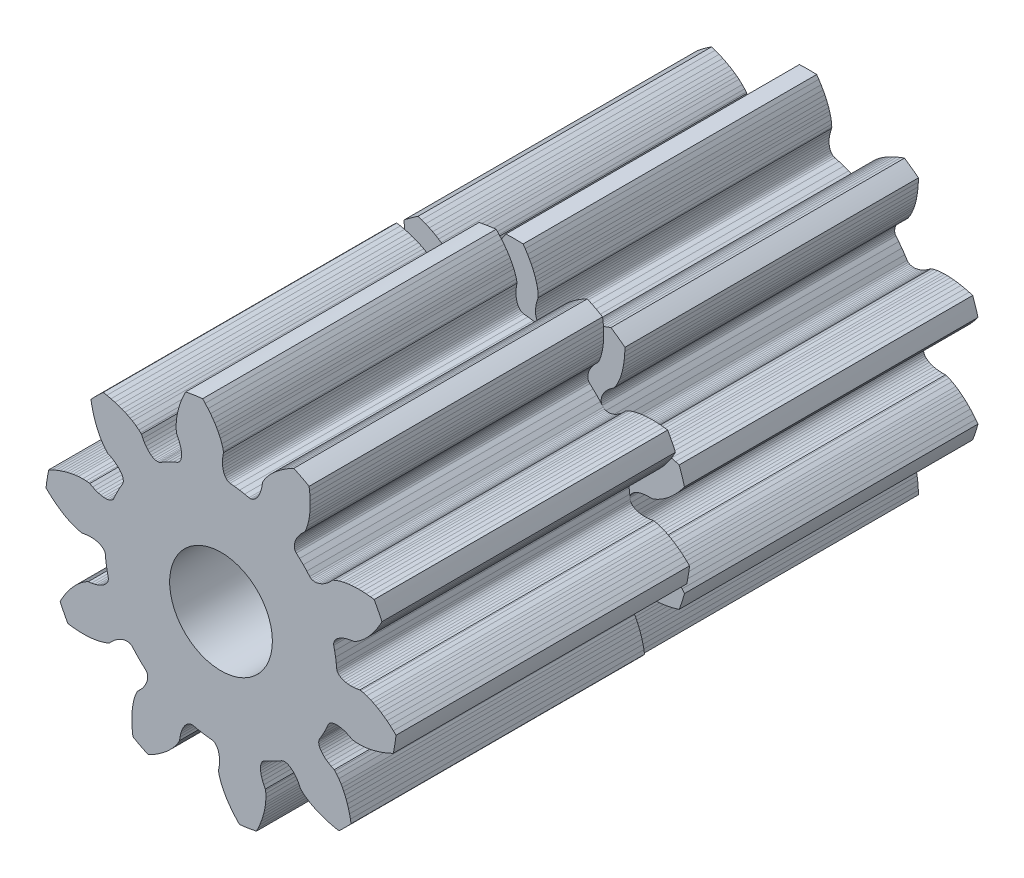
SolidWorks part; units mm, degrees
ref_plane "Front Plane" through (0, 0, 0) normal (0, 0, 1) x (1, 0, 0)
ref_plane "Top Plane" through (0, 0, 0) normal (0, 1, 0) x (1, 0, 0)
ref_plane "Right Plane" through (0, 0, 0) normal (1, 0, 0) x (0, 0, -1)
sketch "Sketch1" plane through (0, 0, 0) normal (0, 0, 1) x (1, 0, 0)
  line L0 (11.2428, -4.5485) -> (11.2517, -4.4039)
  line L1 (11.2517, -4.4039) -> (11.266, -4.2669)
  line L2 (11.266, -4.2669) -> (11.2847, -4.1393)
  line L3 (11.2847, -4.1393) -> (11.3071, -4.0209)
  line L4 (11.3071, -4.0209) -> (11.3325, -3.912)
  line L5 (11.3325, -3.912) -> (11.3608, -3.8103)
  line L6 (11.3608, -3.8103) -> (11.3897, -3.7211)
  line L7 (11.3897, -3.7211) -> (11.4208, -3.6371)
  line L8 (11.4208, -3.6371) -> (11.4807, -3.5016)
  line L9 (11.4807, -3.5016) -> (11.5377, -3.3971)
  line L10 (11.5377, -3.3971) -> (11.5845, -3.3262)
  line L11 (11.5845, -3.3262) -> (11.6076, -3.2964)
  line L12 (11.6076, -3.2964) -> (11.7007, -3.2317)
  line L13 (11.7007, -3.2317) -> (11.7827, -3.1653)
  line L14 (11.7827, -3.1653) -> (11.8533, -3.098)
  line L15 (11.8533, -3.098) -> (11.9128, -3.0308)
  line L16 (11.9128, -3.0308) -> (11.9612, -2.9643)
  line L17 (11.9612, -2.9643) -> (11.9989, -2.8995)
  line L18 (11.9989, -2.8995) -> (12.0259, -2.837)
  line L19 (12.0259, -2.837) -> (12.0426, -2.7776)
  line L20 (12.0426, -2.7776) -> (12.0493, -2.7222)
  line L21 (12.0493, -2.7222) -> (12.0463, -2.6714)
  line L22 (12.0463, -2.6714) -> (12.0342, -2.6259)
  line L23 (12.0342, -2.6259) -> (12.0067, -2.5776)
  line L24 (12.0067, -2.5776) -> (11.9109, -2.4617)
  line L25 (11.9109, -2.4617) -> (11.8044, -2.3217)
  line L26 (11.8044, -2.3217) -> (11.7041, -2.1772)
  line L27 (11.7041, -2.1772) -> (11.6236, -2.0503)
  line L28 (11.6236, -2.0503) -> (11.5861, -2.0092)
  line L29 (11.5861, -2.0092) -> (11.5466, -1.9836)
  line L30 (11.5466, -1.9836) -> (11.4992, -1.9651)
  line L31 (11.4992, -1.9651) -> (11.4444, -1.9543)
  line L32 (11.4444, -1.9543) -> (11.3828, -1.9518)
  line L33 (11.3828, -1.9518) -> (11.315, -1.9582)
  line L34 (11.315, -1.9582) -> (11.2417, -1.974)
  line L35 (11.2417, -1.974) -> (11.1635, -1.9995)
  line L36 (11.1635, -1.9995) -> (11.0812, -2.0353)
  line L37 (11.0812, -2.0353) -> (10.9954, -2.0817)
  line L38 (10.9954, -2.0817) -> (10.907, -2.1391)
  line L39 (10.907, -2.1391) -> (10.8166, -2.2077)
  line L40 (10.8166, -2.2077) -> (10.7811, -2.2204)
  line L41 (10.7811, -2.2204) -> (10.6992, -2.243)
  line L42 (10.6992, -2.243) -> (10.5823, -2.2649)
  line L43 (10.5823, -2.2649) -> (10.4348, -2.2801)
  line L44 (10.4348, -2.2801) -> (10.3453, -2.2837)
  line L45 (10.3453, -2.2837) -> (10.2516, -2.2836)
  line L46 (10.2516, -2.2836) -> (10.1461, -2.2791)
  line L47 (10.1461, -2.2791) -> (10.0348, -2.2696)
  line L48 (10.0348, -2.2696) -> (9.9151, -2.2543)
  line L49 (9.9151, -2.2543) -> (9.7881, -2.2327)
  line L50 (9.7881, -2.2327) -> (9.6533, -2.2039)
  line L51 (9.6533, -2.2039) -> (9.5131, -2.1677)
  line L52 (9.5131, -2.1677) -> (9.3912, -2.1311)
  line L53 (9.2098, -1.5726) -> (9.2868, -1.4714)
  line L54 (9.2868, -1.4714) -> (9.379, -1.3597)
  line L55 (9.379, -1.3597) -> (9.4711, -1.2572)
  line L56 (9.4711, -1.2572) -> (9.5612, -1.165)
  line L57 (9.5612, -1.165) -> (9.649, -1.0823)
  line L58 (9.649, -1.0823) -> (9.7335, -1.0092)
  line L59 (9.7335, -1.0092) -> (9.8162, -0.9435)
  line L60 (9.8162, -0.9435) -> (9.8919, -0.8883)
  line L61 (9.8919, -0.8883) -> (9.9665, -0.8387)
  line L62 (9.9665, -0.8387) -> (10.0947, -0.7642)
  line L63 (10.0947, -0.7642) -> (10.2021, -0.7133)
  line L64 (10.2021, -0.7133) -> (10.2817, -0.6834)
  line L65 (10.2817, -0.6834) -> (10.3179, -0.6728)
  line L66 (10.3179, -0.6728) -> (10.4313, -0.6752)
  line L67 (10.4313, -0.6752) -> (10.5366, -0.6696)
  line L68 (10.5366, -0.6696) -> (10.6333, -0.6568)
  line L69 (10.6333, -0.6568) -> (10.7209, -0.6373)
  line L70 (10.7209, -0.6373) -> (10.7992, -0.612)
  line L71 (10.7992, -0.612) -> (10.8678, -0.5817)
  line L72 (10.8678, -0.5817) -> (10.9263, -0.547)
  line L73 (10.9263, -0.547) -> (10.9747, -0.5088)
  line L74 (10.9747, -0.5088) -> (11.0127, -0.4679)
  line L75 (11.0127, -0.4679) -> (11.0402, -0.4251)
  line L76 (11.0402, -0.4251) -> (11.0571, -0.3811)
  line L77 (11.0571, -0.3811) -> (11.0633, -0.3259)
  line L78 (11.0633, -0.3259) -> (11.0539, -0.1759)
  line L79 (11.0539, -0.1759) -> (11.05, 0)
  line L80 (11.05, 0) -> (11.0539, 0.1759)
  line L81 (11.0539, 0.1759) -> (11.0633, 0.3259)
  line L82 (11.0633, 0.3259) -> (11.0571, 0.3812)
  line L83 (11.0571, 0.3812) -> (11.0402, 0.4251)
  line L84 (11.0402, 0.4251) -> (11.0127, 0.468)
  line L85 (11.0127, 0.468) -> (10.9747, 0.5089)
  line L86 (10.9747, 0.5089) -> (10.9263, 0.5471)
  line L87 (10.9263, 0.5471) -> (10.8678, 0.5817)
  line L88 (10.8678, 0.5817) -> (10.7992, 0.6121)
  line L89 (10.7992, 0.6121) -> (10.7209, 0.6374)
  line L90 (10.7209, 0.6374) -> (10.6333, 0.6568)
  line L91 (10.6333, 0.6568) -> (10.5366, 0.6697)
  line L92 (10.5366, 0.6697) -> (10.4313, 0.6753)
  line L93 (10.4313, 0.6753) -> (10.3179, 0.6729)
  line L94 (10.3179, 0.6729) -> (10.2817, 0.6834)
  line L95 (10.2817, 0.6834) -> (10.2021, 0.7133)
  line L96 (10.2021, 0.7133) -> (10.0947, 0.7643)
  line L97 (10.0947, 0.7643) -> (9.9665, 0.8387)
  line L98 (9.9665, 0.8387) -> (9.8919, 0.8884)
  line L99 (9.8919, 0.8884) -> (9.8162, 0.9436)
  line L100 (9.8162, 0.9436) -> (9.7335, 1.0093)
  line L101 (9.7335, 1.0093) -> (9.649, 1.0824)
  line L102 (9.649, 1.0824) -> (9.5612, 1.165)
  line L103 (9.5612, 1.165) -> (9.4711, 1.2572)
  line L104 (9.4711, 1.2572) -> (9.379, 1.3597)
  line L105 (9.379, 1.3597) -> (9.2868, 1.4714)
  line L106 (9.2868, 1.4714) -> (9.2098, 1.5727)
  line L107 (9.3912, 2.1311) -> (9.5131, 2.1677)
  line L108 (9.5131, 2.1677) -> (9.6533, 2.2039)
  line L109 (9.6533, 2.2039) -> (9.788, 2.2327)
  line L110 (9.788, 2.2327) -> (9.9151, 2.2544)
  line L111 (9.9151, 2.2544) -> (10.0347, 2.2696)
  line L112 (10.0347, 2.2696) -> (10.1461, 2.2791)
  line L113 (10.1461, 2.2791) -> (10.2516, 2.2836)
  line L114 (10.2516, 2.2836) -> (10.3453, 2.2837)
  line L115 (10.3453, 2.2837) -> (10.4348, 2.2801)
  line L116 (10.4348, 2.2801) -> (10.5823, 2.265)
  line L117 (10.5823, 2.265) -> (10.6992, 2.2431)
  line L118 (10.6992, 2.2431) -> (10.7811, 2.2205)
  line L119 (10.7811, 2.2205) -> (10.8166, 2.2078)
  line L120 (10.8166, 2.2078) -> (10.9069, 2.1391)
  line L121 (10.9069, 2.1391) -> (10.9954, 2.0818)
  line L122 (10.9954, 2.0818) -> (11.0812, 2.0353)
  line L123 (11.0812, 2.0353) -> (11.1635, 1.9995)
  line L124 (11.1635, 1.9995) -> (11.2417, 1.974)
  line L125 (11.2417, 1.974) -> (11.315, 1.9583)
  line L126 (11.315, 1.9583) -> (11.3828, 1.9519)
  line L127 (11.3828, 1.9519) -> (11.4444, 1.9543)
  line L128 (11.4444, 1.9543) -> (11.4991, 1.9651)
  line L129 (11.4991, 1.9651) -> (11.5465, 1.9836)
  line L130 (11.5465, 1.9836) -> (11.586, 2.0092)
  line L131 (11.586, 2.0092) -> (11.6235, 2.0503)
  line L132 (11.6235, 2.0503) -> (11.7041, 2.1772)
  line L133 (11.7041, 2.1772) -> (11.8043, 2.3218)
  line L134 (11.8043, 2.3218) -> (11.9109, 2.4618)
  line L135 (11.9109, 2.4618) -> (12.0067, 2.5776)
  line L136 (12.0067, 2.5776) -> (12.0341, 2.626)
  line L137 (12.0341, 2.626) -> (12.0463, 2.6715)
  line L138 (12.0463, 2.6715) -> (12.0492, 2.7223)
  line L139 (12.0492, 2.7223) -> (12.0426, 2.7777)
  line L140 (12.0426, 2.7777) -> (12.0259, 2.837)
  line L141 (12.0259, 2.837) -> (11.9988, 2.8995)
  line L142 (11.9988, 2.8995) -> (11.9612, 2.9643)
  line L143 (11.9612, 2.9643) -> (11.9128, 3.0308)
  line L144 (11.9128, 3.0308) -> (11.8533, 3.0981)
  line L145 (11.8533, 3.0981) -> (11.7826, 3.1653)
  line L146 (11.7826, 3.1653) -> (11.7007, 3.2317)
  line L147 (11.7007, 3.2317) -> (11.6075, 3.2964)
  line L148 (11.6075, 3.2964) -> (11.5845, 3.3262)
  line L149 (11.5845, 3.3262) -> (11.5377, 3.3972)
  line L150 (11.5377, 3.3972) -> (11.4807, 3.5016)
  line L151 (11.4807, 3.5016) -> (11.4208, 3.6372)
  line L152 (11.4208, 3.6372) -> (11.3896, 3.7212)
  line L153 (11.3896, 3.7212) -> (11.3608, 3.8103)
  line L154 (11.3608, 3.8103) -> (11.3325, 3.9121)
  line L155 (11.3325, 3.9121) -> (11.3071, 4.0209)
  line L156 (11.3071, 4.0209) -> (11.2846, 4.1394)
  line L157 (11.2846, 4.1394) -> (11.2659, 4.2669)
  line L158 (11.2659, 4.2669) -> (11.2517, 4.404)
  line L159 (11.2517, 4.404) -> (11.2428, 4.5485)
  line L160 (11.2428, 4.5485) -> (11.2399, 4.6757)
  line L161 (11.715, 5.0209) -> (11.8351, 4.9789)
  line L162 (11.8351, 4.9789) -> (11.9698, 4.9257)
  line L163 (11.9698, 4.9257) -> (12.0958, 4.8698)
  line L164 (12.0958, 4.8698) -> (12.2113, 4.8127)
  line L165 (12.2113, 4.8127) -> (12.3171, 4.7547)
  line L166 (12.3171, 4.7547) -> (12.4127, 4.6969)
  line L167 (12.4127, 4.6969) -> (12.5007, 4.6385)
  line L168 (12.5007, 4.6385) -> (12.5766, 4.5836)
  line L169 (12.5766, 4.5836) -> (12.6469, 4.528)
  line L170 (12.6469, 4.528) -> (12.7573, 4.4291)
  line L171 (12.7573, 4.4291) -> (12.839, 4.3427)
  line L172 (12.839, 4.3427) -> (12.892, 4.2762)
  line L173 (12.892, 4.2762) -> (12.9132, 4.2451)
  line L174 (12.9132, 4.2451) -> (12.946, 4.1364)
  line L175 (12.946, 4.1364) -> (12.9838, 4.038)
  line L176 (12.9838, 4.038) -> (13.0259, 3.9501)
  line L177 (13.0259, 3.9501) -> (13.0715, 3.8727)
  line L178 (13.0715, 3.8727) -> (13.1197, 3.8061)
  line L179 (13.1197, 3.8061) -> (13.1698, 3.7503)
  line L180 (13.1698, 3.7503) -> (13.2209, 3.7053)
  line L181 (13.2209, 3.7053) -> (13.2721, 3.671)
  line L182 (13.2721, 3.671) -> (13.3228, 3.6476)
  line L183 (13.3228, 3.6476) -> (13.372, 3.6347)
  line L184 (13.372, 3.6347) -> (13.419, 3.6322)
  line L185 (13.419, 3.6322) -> (13.4735, 3.6434)
  line L186 (13.4735, 3.6434) -> (13.6133, 3.6987)
  line L187 (13.6133, 3.6987) -> (13.7794, 3.7567)
  line L188 (13.7794, 3.7567) -> (13.9478, 3.8074)
  line L189 (13.9478, 3.8074) -> (14.0934, 3.8448)
  line L190 (14.0934, 3.8448) -> (14.1441, 3.8678)
  line L191 (14.1441, 3.8678) -> (14.1806, 3.8974)
  line L192 (14.1806, 3.8974) -> (14.2129, 3.9368)
  line L193 (14.2129, 3.9368) -> (14.2401, 3.9855)
  line L194 (14.2401, 3.9855) -> (14.2614, 4.0434)
  line L195 (14.2614, 4.0434) -> (14.2763, 4.1098)
  line L196 (14.2763, 4.1098) -> (14.284, 4.1844)
  line L197 (14.284, 4.1844) -> (14.2838, 4.2666)
  line L198 (14.2838, 4.2666) -> (14.2752, 4.356)
  line L199 (14.2752, 4.356) -> (14.2576, 4.4519)
  line L200 (14.2576, 4.4519) -> (14.2304, 4.5538)
  line L201 (14.2304, 4.5538) -> (14.193, 4.6609)
  line L202 (14.193, 4.6609) -> (14.1919, 4.6986)
  line L203 (14.1919, 4.6986) -> (14.1957, 4.7835)
  line L204 (14.1957, 4.7835) -> (14.211, 4.9014)
  line L205 (14.211, 4.9014) -> (14.2422, 5.0463)
  line L206 (14.2422, 5.0463) -> (14.2664, 5.1326)
  line L207 (14.2664, 5.1326) -> (14.2955, 5.2217)
  line L208 (14.2955, 5.2217) -> (14.3324, 5.3207)
  line L209 (14.3324, 5.3207) -> (14.3758, 5.4236)
  line L210 (14.3758, 5.4236) -> (14.4273, 5.5327)
  line L211 (14.4273, 5.5327) -> (14.4871, 5.6468)
  line L212 (14.4871, 5.6468) -> (14.5562, 5.7661)
  line L213 (14.5562, 5.7661) -> (14.6339, 5.8883)
  line L214 (14.6339, 5.8883) -> (14.7064, 5.9928)
  line L215 (15.2936, 5.9928) -> (15.3661, 5.8883)
  line L216 (15.3661, 5.8883) -> (15.4438, 5.7661)
  line L217 (15.4438, 5.7661) -> (15.5128, 5.6468)
  line L218 (15.5128, 5.6468) -> (15.5727, 5.5327)
  line L219 (15.5727, 5.5327) -> (15.6242, 5.4236)
  line L220 (15.6242, 5.4236) -> (15.6676, 5.3207)
  line L221 (15.6676, 5.3207) -> (15.7045, 5.2217)
  line L222 (15.7045, 5.2217) -> (15.7336, 5.1326)
  line L223 (15.7336, 5.1326) -> (15.7578, 5.0464)
  line L224 (15.7578, 5.0464) -> (15.7889, 4.9014)
  line L225 (15.7889, 4.9014) -> (15.8042, 4.7835)
  line L226 (15.8042, 4.7835) -> (15.8081, 4.6986)
  line L227 (15.8081, 4.6986) -> (15.8069, 4.6609)
  line L228 (15.8069, 4.6609) -> (15.7696, 4.5538)
  line L229 (15.7696, 4.5538) -> (15.7424, 4.4519)
  line L230 (15.7424, 4.4519) -> (15.7247, 4.356)
  line L231 (15.7247, 4.356) -> (15.7161, 4.2666)
  line L232 (15.7161, 4.2666) -> (15.716, 4.1844)
  line L233 (15.716, 4.1844) -> (15.7237, 4.1098)
  line L234 (15.7237, 4.1098) -> (15.7385, 4.0434)
  line L235 (15.7385, 4.0434) -> (15.7599, 3.9855)
  line L236 (15.7599, 3.9855) -> (15.7871, 3.9368)
  line L237 (15.7871, 3.9368) -> (15.8193, 3.8974)
  line L238 (15.8193, 3.8974) -> (15.8559, 3.8678)
  line L239 (15.8559, 3.8678) -> (15.9065, 3.8448)
  line L240 (15.9065, 3.8448) -> (16.0521, 3.8074)
  line L241 (16.0521, 3.8074) -> (16.2206, 3.7567)
  line L242 (16.2206, 3.7567) -> (16.3867, 3.6987)
  line L243 (16.3867, 3.6987) -> (16.5264, 3.6434)
  line L244 (16.5264, 3.6434) -> (16.5809, 3.6322)
  line L245 (16.5809, 3.6322) -> (16.6279, 3.6347)
  line L246 (16.6279, 3.6347) -> (16.6772, 3.6476)
  line L247 (16.6772, 3.6476) -> (16.7278, 3.6711)
  line L248 (16.7278, 3.6711) -> (16.7791, 3.7053)
  line L249 (16.7791, 3.7053) -> (16.8301, 3.7503)
  line L250 (16.8301, 3.7503) -> (16.8802, 3.8061)
  line L251 (16.8802, 3.8061) -> (16.9284, 3.8727)
  line L252 (16.9284, 3.8727) -> (16.974, 3.9501)
  line L253 (16.974, 3.9501) -> (17.0161, 4.038)
  line L254 (17.0161, 4.038) -> (17.054, 4.1365)
  line L255 (17.054, 4.1365) -> (17.0867, 4.2451)
  line L256 (17.0867, 4.2451) -> (17.108, 4.2762)
  line L257 (17.108, 4.2762) -> (17.161, 4.3427)
  line L258 (17.161, 4.3427) -> (17.2427, 4.4291)
  line L259 (17.2427, 4.4291) -> (17.3531, 4.528)
  line L260 (17.3531, 4.528) -> (17.4233, 4.5836)
  line L261 (17.4233, 4.5836) -> (17.4992, 4.6385)
  line L262 (17.4992, 4.6385) -> (17.5873, 4.6969)
  line L263 (17.5873, 4.6969) -> (17.6829, 4.7547)
  line L264 (17.6829, 4.7547) -> (17.7886, 4.8127)
  line L265 (17.7886, 4.8127) -> (17.9042, 4.8699)
  line L266 (17.9042, 4.8699) -> (18.0301, 4.9258)
  line L267 (18.0301, 4.9258) -> (18.1648, 4.9789)
  line L268 (18.1648, 4.9789) -> (18.2849, 5.0209)
  line L269 (18.76, 4.6758) -> (18.7572, 4.5486)
  line L270 (18.7572, 4.5486) -> (18.7483, 4.404)
  line L271 (18.7483, 4.404) -> (18.734, 4.2669)
  line L272 (18.734, 4.2669) -> (18.7153, 4.1394)
  line L273 (18.7153, 4.1394) -> (18.6928, 4.0209)
  line L274 (18.6928, 4.0209) -> (18.6675, 3.9121)
  line L275 (18.6675, 3.9121) -> (18.6392, 3.8103)
  line L276 (18.6392, 3.8103) -> (18.6103, 3.7212)
  line L277 (18.6103, 3.7212) -> (18.5792, 3.6372)
  line L278 (18.5792, 3.6372) -> (18.5192, 3.5016)
  line L279 (18.5192, 3.5016) -> (18.4623, 3.3972)
  line L280 (18.4623, 3.3972) -> (18.4155, 3.3263)
  line L281 (18.4155, 3.3263) -> (18.3924, 3.2965)
  line L282 (18.3924, 3.2965) -> (18.2992, 3.2317)
  line L283 (18.2992, 3.2317) -> (18.2173, 3.1653)
  line L284 (18.2173, 3.1653) -> (18.1467, 3.0981)
  line L285 (18.1467, 3.0981) -> (18.0872, 3.0308)
  line L286 (18.0872, 3.0308) -> (18.0387, 2.9644)
  line L287 (18.0387, 2.9644) -> (18.0011, 2.8995)
  line L288 (18.0011, 2.8995) -> (17.9741, 2.837)
  line L289 (17.9741, 2.837) -> (17.9574, 2.7777)
  line L290 (17.9574, 2.7777) -> (17.9507, 2.7223)
  line L291 (17.9507, 2.7223) -> (17.9537, 2.6715)
  line L292 (17.9537, 2.6715) -> (17.9658, 2.626)
  line L293 (17.9658, 2.626) -> (17.9933, 2.5777)
  line L294 (17.9933, 2.5777) -> (18.0891, 2.4618)
  line L295 (18.0891, 2.4618) -> (18.1956, 2.3218)
  line L296 (18.1956, 2.3218) -> (18.2959, 2.1772)
  line L297 (18.2959, 2.1772) -> (18.3764, 2.0503)
  line L298 (18.3764, 2.0503) -> (18.4139, 2.0093)
  line L299 (18.4139, 2.0093) -> (18.4534, 1.9836)
  line L300 (18.4534, 1.9836) -> (18.5008, 1.9651)
  line L301 (18.5008, 1.9651) -> (18.5556, 1.9544)
  line L302 (18.5556, 1.9544) -> (18.6172, 1.9519)
  line L303 (18.6172, 1.9519) -> (18.6849, 1.9583)
  line L304 (18.6849, 1.9583) -> (18.7583, 1.974)
  line L305 (18.7583, 1.974) -> (18.8364, 1.9996)
  line L306 (18.8364, 1.9996) -> (18.9188, 2.0354)
  line L307 (18.9188, 2.0354) -> (19.0046, 2.0818)
  line L308 (19.0046, 2.0818) -> (19.093, 2.1392)
  line L309 (19.093, 2.1392) -> (19.1834, 2.2078)
  line L310 (19.1834, 2.2078) -> (19.2188, 2.2205)
  line L311 (19.2188, 2.2205) -> (19.3008, 2.2431)
  line L312 (19.3008, 2.2431) -> (19.4177, 2.265)
  line L313 (19.4177, 2.265) -> (19.5651, 2.2801)
  line L314 (19.5651, 2.2801) -> (19.6547, 2.2838)
  line L315 (19.6547, 2.2838) -> (19.7484, 2.2837)
  line L316 (19.7484, 2.2837) -> (19.8539, 2.2791)
  line L317 (19.8539, 2.2791) -> (19.9652, 2.2696)
  line L318 (19.9652, 2.2696) -> (20.0848, 2.2544)
  line L319 (20.0848, 2.2544) -> (20.2119, 2.2328)
  line L320 (20.2119, 2.2328) -> (20.3467, 2.204)
  line L321 (20.3467, 2.204) -> (20.4869, 2.1678)
  line L322 (20.4869, 2.1678) -> (20.6088, 2.1312)
  line L323 (20.7902, 1.5727) -> (20.7132, 1.4714)
  line L324 (20.7132, 1.4714) -> (20.621, 1.3598)
  line L325 (20.621, 1.3598) -> (20.5289, 1.2572)
  line L326 (20.5289, 1.2572) -> (20.4388, 1.165)
  line L327 (20.4388, 1.165) -> (20.351, 1.0824)
  line L328 (20.351, 1.0824) -> (20.2665, 1.0093)
  line L329 (20.2665, 1.0093) -> (20.1838, 0.9436)
  line L330 (20.1838, 0.9436) -> (20.108, 0.8884)
  line L331 (20.108, 0.8884) -> (20.0335, 0.8388)
  line L332 (20.0335, 0.8388) -> (19.9053, 0.7643)
  line L333 (19.9053, 0.7643) -> (19.7979, 0.7133)
  line L334 (19.7979, 0.7133) -> (19.7183, 0.6834)
  line L335 (19.7183, 0.6834) -> (19.6821, 0.6729)
  line L336 (19.6821, 0.6729) -> (19.5687, 0.6753)
  line L337 (19.5687, 0.6753) -> (19.4634, 0.6697)
  line L338 (19.4634, 0.6697) -> (19.3667, 0.6568)
  line L339 (19.3667, 0.6568) -> (19.279, 0.6374)
  line L340 (19.279, 0.6374) -> (19.2008, 0.6121)
  line L341 (19.2008, 0.6121) -> (19.1322, 0.5818)
  line L342 (19.1322, 0.5818) -> (19.0736, 0.5471)
  line L343 (19.0736, 0.5471) -> (19.0253, 0.5089)
  line L344 (19.0253, 0.5089) -> (18.9873, 0.468)
  line L345 (18.9873, 0.468) -> (18.9598, 0.4252)
  line L346 (18.9598, 0.4252) -> (18.9429, 0.3812)
  line L347 (18.9429, 0.3812) -> (18.9367, 0.3259)
  line L348 (18.9367, 0.3259) -> (18.9461, 0.1759)
  line L349 (18.9461, 0.1759) -> (18.95, 0)
  line L350 (18.95, 0) -> (18.9461, -0.1758)
  line L351 (18.9461, -0.1758) -> (18.9367, -0.3259)
  line L352 (18.9367, -0.3259) -> (18.9429, -0.3811)
  line L353 (18.9429, -0.3811) -> (18.9598, -0.4251)
  line L354 (18.9598, -0.4251) -> (18.9873, -0.4679)
  line L355 (18.9873, -0.4679) -> (19.0253, -0.5088)
  line L356 (19.0253, -0.5088) -> (19.0736, -0.547)
  line L357 (19.0736, -0.547) -> (19.1322, -0.5817)
  line L358 (19.1322, -0.5817) -> (19.2008, -0.612)
  line L359 (19.2008, -0.612) -> (19.279, -0.6373)
  line L360 (19.279, -0.6373) -> (19.3667, -0.6567)
  line L361 (19.3667, -0.6567) -> (19.4634, -0.6696)
  line L362 (19.4634, -0.6696) -> (19.5687, -0.6752)
  line L363 (19.5687, -0.6752) -> (19.6821, -0.6728)
  line L364 (19.6821, -0.6728) -> (19.7183, -0.6834)
  line L365 (19.7183, -0.6834) -> (19.7979, -0.7132)
  line L366 (19.7979, -0.7132) -> (19.9053, -0.7642)
  line L367 (19.9053, -0.7642) -> (20.0335, -0.8387)
  line L368 (20.0335, -0.8387) -> (20.108, -0.8883)
  line L369 (20.108, -0.8883) -> (20.1838, -0.9435)
  line L370 (20.1838, -0.9435) -> (20.2665, -1.0092)
  line L371 (20.2665, -1.0092) -> (20.351, -1.0823)
  line L372 (20.351, -1.0823) -> (20.4388, -1.1649)
  line L373 (20.4388, -1.1649) -> (20.5289, -1.2571)
  line L374 (20.5289, -1.2571) -> (20.621, -1.3597)
  line L375 (20.621, -1.3597) -> (20.7132, -1.4714)
  line L376 (20.7132, -1.4714) -> (20.7902, -1.5726)
  line L377 (20.6088, -2.131) -> (20.4869, -2.1677)
  line L378 (20.4869, -2.1677) -> (20.3467, -2.2039)
  line L379 (20.3467, -2.2039) -> (20.2119, -2.2327)
  line L380 (20.2119, -2.2327) -> (20.0849, -2.2543)
  line L381 (20.0849, -2.2543) -> (19.9652, -2.2695)
  line L382 (19.9652, -2.2695) -> (19.8539, -2.279)
  line L383 (19.8539, -2.279) -> (19.7484, -2.2836)
  line L384 (19.7484, -2.2836) -> (19.6547, -2.2837)
  line L385 (19.6547, -2.2837) -> (19.5652, -2.28)
  line L386 (19.5652, -2.28) -> (19.4177, -2.2649)
  line L387 (19.4177, -2.2649) -> (19.3008, -2.243)
  line L388 (19.3008, -2.243) -> (19.2189, -2.2204)
  line L389 (19.2189, -2.2204) -> (19.1834, -2.2077)
  line L390 (19.1834, -2.2077) -> (19.093, -2.1391)
  line L391 (19.093, -2.1391) -> (19.0046, -2.0817)
  line L392 (19.0046, -2.0817) -> (18.9188, -2.0353)
  line L393 (18.9188, -2.0353) -> (18.8365, -1.9995)
  line L394 (18.8365, -1.9995) -> (18.7583, -1.9739)
  line L395 (18.7583, -1.9739) -> (18.685, -1.9582)
  line L396 (18.685, -1.9582) -> (18.6172, -1.9518)
  line L397 (18.6172, -1.9518) -> (18.5556, -1.9543)
  line L398 (18.5556, -1.9543) -> (18.5008, -1.965)
  line L399 (18.5008, -1.965) -> (18.4534, -1.9835)
  line L400 (18.4534, -1.9835) -> (18.4139, -2.0092)
  line L401 (18.4139, -2.0092) -> (18.3764, -2.0502)
  line L402 (18.3764, -2.0502) -> (18.2959, -2.1771)
  line L403 (18.2959, -2.1771) -> (18.1956, -2.3217)
  line L404 (18.1956, -2.3217) -> (18.0891, -2.4617)
  line L405 (18.0891, -2.4617) -> (17.9933, -2.5776)
  line L406 (17.9933, -2.5776) -> (17.9658, -2.6259)
  line L407 (17.9658, -2.6259) -> (17.9537, -2.6714)
  line L408 (17.9537, -2.6714) -> (17.9507, -2.7222)
  line L409 (17.9507, -2.7222) -> (17.9574, -2.7776)
  line L410 (17.9574, -2.7776) -> (17.9741, -2.8369)
  line L411 (17.9741, -2.8369) -> (18.0011, -2.8994)
  line L412 (18.0011, -2.8994) -> (18.0387, -2.9643)
  line L413 (18.0387, -2.9643) -> (18.0872, -3.0307)
  line L414 (18.0872, -3.0307) -> (18.1467, -3.098)
  line L415 (18.1467, -3.098) -> (18.2173, -3.1652)
  line L416 (18.2173, -3.1652) -> (18.2992, -3.2316)
  line L417 (18.2992, -3.2316) -> (18.3924, -3.2964)
  line L418 (18.3924, -3.2964) -> (18.4155, -3.3262)
  line L419 (18.4155, -3.3262) -> (18.4623, -3.3971)
  line L420 (18.4623, -3.3971) -> (18.5193, -3.5015)
  line L421 (18.5193, -3.5015) -> (18.5792, -3.6371)
  line L422 (18.5792, -3.6371) -> (18.6103, -3.7211)
  line L423 (18.6103, -3.7211) -> (18.6392, -3.8102)
  line L424 (18.6392, -3.8102) -> (18.6675, -3.912)
  line L425 (18.6675, -3.912) -> (18.6929, -4.0208)
  line L426 (18.6929, -4.0208) -> (18.7153, -4.1393)
  line L427 (18.7153, -4.1393) -> (18.734, -4.2668)
  line L428 (18.734, -4.2668) -> (18.7483, -4.4039)
  line L429 (18.7483, -4.4039) -> (18.7572, -4.5484)
  line L430 (18.7572, -4.5484) -> (18.76, -4.6757)
  line L431 (18.285, -5.0208) -> (18.1648, -4.9788)
  line L432 (18.1648, -4.9788) -> (18.0301, -4.9257)
  line L433 (18.0301, -4.9257) -> (17.9042, -4.8698)
  line L434 (17.9042, -4.8698) -> (17.7886, -4.8126)
  line L435 (17.7886, -4.8126) -> (17.6829, -4.7546)
  line L436 (17.6829, -4.7546) -> (17.5873, -4.6968)
  line L437 (17.5873, -4.6968) -> (17.4992, -4.6385)
  line L438 (17.4992, -4.6385) -> (17.4234, -4.5835)
  line L439 (17.4234, -4.5835) -> (17.3531, -4.5279)
  line L440 (17.3531, -4.5279) -> (17.2427, -4.429)
  line L441 (17.2427, -4.429) -> (17.161, -4.3426)
  line L442 (17.161, -4.3426) -> (17.108, -4.2761)
  line L443 (17.108, -4.2761) -> (17.0868, -4.245)
  line L444 (17.0868, -4.245) -> (17.054, -4.1364)
  line L445 (17.054, -4.1364) -> (17.0161, -4.038)
  line L446 (17.0161, -4.038) -> (16.974, -3.95)
  line L447 (16.974, -3.95) -> (16.9284, -3.8726)
  line L448 (16.9284, -3.8726) -> (16.8802, -3.806)
  line L449 (16.8802, -3.806) -> (16.8302, -3.7502)
  line L450 (16.8302, -3.7502) -> (16.7791, -3.7052)
  line L451 (16.7791, -3.7052) -> (16.7278, -3.671)
  line L452 (16.7278, -3.671) -> (16.6772, -3.6475)
  line L453 (16.6772, -3.6475) -> (16.6279, -3.6346)
  line L454 (16.6279, -3.6346) -> (16.5809, -3.6321)
  line L455 (16.5809, -3.6321) -> (16.5265, -3.6433)
  line L456 (16.5265, -3.6433) -> (16.3867, -3.6986)
  line L457 (16.3867, -3.6986) -> (16.2206, -3.7567)
  line L458 (16.2206, -3.7567) -> (16.0521, -3.8073)
  line L459 (16.0521, -3.8073) -> (15.9066, -3.8447)
  line L460 (15.9066, -3.8447) -> (15.8559, -3.8677)
  line L461 (15.8559, -3.8677) -> (15.8193, -3.8973)
  line L462 (15.8193, -3.8973) -> (15.7871, -3.9367)
  line L463 (15.7871, -3.9367) -> (15.7599, -3.9855)
  line L464 (15.7599, -3.9855) -> (15.7385, -4.0433)
  line L465 (15.7385, -4.0433) -> (15.7237, -4.1097)
  line L466 (15.7237, -4.1097) -> (15.716, -4.1843)
  line L467 (15.716, -4.1843) -> (15.7161, -4.2665)
  line L468 (15.7161, -4.2665) -> (15.7247, -4.3559)
  line L469 (15.7247, -4.3559) -> (15.7424, -4.4518)
  line L470 (15.7424, -4.4518) -> (15.7696, -4.5537)
  line L471 (15.7696, -4.5537) -> (15.8069, -4.6609)
  line L472 (15.8069, -4.6609) -> (15.8081, -4.6985)
  line L473 (15.8081, -4.6985) -> (15.8042, -4.7834)
  line L474 (15.8042, -4.7834) -> (15.789, -4.9014)
  line L475 (15.789, -4.9014) -> (15.7578, -5.0463)
  line L476 (15.7578, -5.0463) -> (15.7336, -5.1325)
  line L477 (15.7336, -5.1325) -> (15.7045, -5.2216)
  line L478 (15.7045, -5.2216) -> (15.6676, -5.3206)
  line L479 (15.6676, -5.3206) -> (15.6242, -5.4235)
  line L480 (15.6242, -5.4235) -> (15.5727, -5.5326)
  line L481 (15.5727, -5.5326) -> (15.5129, -5.6468)
  line L482 (15.5129, -5.6468) -> (15.4438, -5.766)
  line L483 (15.4438, -5.766) -> (15.3661, -5.8882)
  line L484 (15.3661, -5.8882) -> (15.2936, -5.9928)
  line L485 (14.7064, -5.9928) -> (14.6339, -5.8882)
  line L486 (14.6339, -5.8882) -> (14.5561, -5.766)
  line L487 (14.5561, -5.766) -> (14.4871, -5.6468)
  line L488 (14.4871, -5.6468) -> (14.4272, -5.5326)
  line L489 (14.4272, -5.5326) -> (14.3758, -5.4235)
  line L490 (14.3758, -5.4235) -> (14.3324, -5.3206)
  line L491 (14.3324, -5.3206) -> (14.2954, -5.2216)
  line L492 (14.2954, -5.2216) -> (14.2664, -5.1325)
  line L493 (14.2664, -5.1325) -> (14.2422, -5.0463)
  line L494 (14.2422, -5.0463) -> (14.211, -4.9014)
  line L495 (14.211, -4.9014) -> (14.1957, -4.7834)
  line L496 (14.1957, -4.7834) -> (14.1919, -4.6985)
  line L497 (14.1919, -4.6985) -> (14.193, -4.6608)
  line L498 (14.193, -4.6608) -> (14.2304, -4.5537)
  line L499 (14.2304, -4.5537) -> (14.2576, -4.4518)
  line L500 (14.2576, -4.4518) -> (14.2752, -4.3559)
  line L501 (14.2752, -4.3559) -> (14.2838, -4.2665)
  line L502 (14.2838, -4.2665) -> (14.284, -4.1843)
  line L503 (14.284, -4.1843) -> (14.2763, -4.1097)
  line L504 (14.2763, -4.1097) -> (14.2614, -4.0433)
  line L505 (14.2614, -4.0433) -> (14.24, -3.9855)
  line L506 (14.24, -3.9855) -> (14.2129, -3.9367)
  line L507 (14.2129, -3.9367) -> (14.1806, -3.8973)
  line L508 (14.1806, -3.8973) -> (14.144, -3.8677)
  line L509 (14.144, -3.8677) -> (14.0934, -3.8447)
  line L510 (14.0934, -3.8447) -> (13.9478, -3.8073)
  line L511 (13.9478, -3.8073) -> (13.7793, -3.7567)
  line L512 (13.7793, -3.7567) -> (13.6133, -3.6986)
  line L513 (13.6133, -3.6986) -> (13.4735, -3.6433)
  line L514 (13.4735, -3.6433) -> (13.419, -3.6321)
  line L515 (13.419, -3.6321) -> (13.372, -3.6346)
  line L516 (13.372, -3.6346) -> (13.3228, -3.6475)
  line L517 (13.3228, -3.6475) -> (13.2721, -3.671)
  line L518 (13.2721, -3.671) -> (13.2209, -3.7052)
  line L519 (13.2209, -3.7052) -> (13.1698, -3.7502)
  line L520 (13.1698, -3.7502) -> (13.1197, -3.806)
  line L521 (13.1197, -3.806) -> (13.0715, -3.8726)
  line L522 (13.0715, -3.8726) -> (13.0259, -3.95)
  line L523 (13.0259, -3.95) -> (12.9838, -4.038)
  line L524 (12.9838, -4.038) -> (12.946, -4.1364)
  line L525 (12.946, -4.1364) -> (12.9132, -4.245)
  line L526 (12.9132, -4.245) -> (12.892, -4.2761)
  line L527 (12.892, -4.2761) -> (12.839, -4.3426)
  line L528 (12.839, -4.3426) -> (12.7573, -4.429)
  line L529 (12.7573, -4.429) -> (12.6469, -4.5279)
  line L530 (12.6469, -4.5279) -> (12.5766, -4.5835)
  line L531 (12.5766, -4.5835) -> (12.5007, -4.6385)
  line L532 (12.5007, -4.6385) -> (12.4127, -4.6968)
  line L533 (12.4127, -4.6968) -> (12.317, -4.7546)
  line L534 (12.317, -4.7546) -> (12.2113, -4.8126)
  line L535 (12.2113, -4.8126) -> (12.0958, -4.8698)
  line L536 (12.0958, -4.8698) -> (11.9698, -4.9257)
  line L537 (11.9698, -4.9257) -> (11.8351, -4.9788)
  line L538 (11.8351, -4.9788) -> (11.715, -5.0208)
  line L539 (11.24, -4.6757) -> (11.2428, -4.5485)
  line L540 (11.2428, -4.5485) -> (11.2517, -4.4039)
  line L541 (11.2517, -4.4039) -> (11.266, -4.2669)
  line L542 (11.266, -4.2669) -> (11.2847, -4.1393)
  line L543 (11.2847, -4.1393) -> (11.3071, -4.0209)
  line L544 (11.3071, -4.0209) -> (11.3325, -3.912)
  line L545 (11.3325, -3.912) -> (11.3608, -3.8103)
  line L546 (11.3608, -3.8103) -> (11.3897, -3.7211)
  line L547 (11.3897, -3.7211) -> (11.4208, -3.6371)
  line L548 (11.4208, -3.6371) -> (11.4807, -3.5016)
  line L549 (11.4807, -3.5016) -> (11.5377, -3.3971)
  line L550 (11.5377, -3.3971) -> (11.5845, -3.3262)
  line L551 (11.5845, -3.3262) -> (11.6076, -3.2964)
  line L552 (11.6076, -3.2964) -> (11.7007, -3.2317)
  line L553 (11.7007, -3.2317) -> (11.7827, -3.1653)
  line L554 (11.7827, -3.1653) -> (11.8533, -3.098)
  line L555 (11.8533, -3.098) -> (11.9128, -3.0308)
  line L556 (11.9128, -3.0308) -> (11.9612, -2.9643)
  line L557 (11.9612, -2.9643) -> (11.9989, -2.8995)
  line L558 (11.9989, -2.8995) -> (12.0259, -2.837)
  line L559 (12.0259, -2.837) -> (12.0426, -2.7776)
  line L560 (12.0426, -2.7776) -> (12.0493, -2.7222)
  line L561 (12.0493, -2.7222) -> (12.0463, -2.6714)
  line L562 (12.0463, -2.6714) -> (12.0342, -2.6259)
  line L563 (12.0342, -2.6259) -> (12.0067, -2.5776)
  line L564 (12.0067, -2.5776) -> (11.9109, -2.4617)
  line L565 (11.9109, -2.4617) -> (11.8044, -2.3217)
  line L566 (11.8044, -2.3217) -> (11.7041, -2.1772)
  line L567 (11.7041, -2.1772) -> (11.6236, -2.0503)
  line L568 (11.6236, -2.0503) -> (11.5861, -2.0092)
  line L569 (11.5861, -2.0092) -> (11.5466, -1.9836)
  line L570 (11.5466, -1.9836) -> (11.4992, -1.9651)
  line L571 (11.4992, -1.9651) -> (11.4444, -1.9543)
  line L572 (11.4444, -1.9543) -> (11.3828, -1.9518)
  line L573 (11.3828, -1.9518) -> (11.315, -1.9582)
  line L574 (11.315, -1.9582) -> (11.2417, -1.974)
  line L575 (11.2417, -1.974) -> (11.1635, -1.9995)
  line L576 (11.1635, -1.9995) -> (11.0812, -2.0353)
  line L577 (11.0812, -2.0353) -> (10.9954, -2.0817)
  line L578 (10.9954, -2.0817) -> (10.907, -2.1391)
  line L579 (10.907, -2.1391) -> (10.8166, -2.2077)
  line L580 (10.8166, -2.2077) -> (10.7811, -2.2204)
  line L581 (10.7811, -2.2204) -> (10.6992, -2.243)
  line L582 (10.6992, -2.243) -> (10.5823, -2.2649)
  line L583 (10.5823, -2.2649) -> (10.4348, -2.2801)
  line L584 (10.4348, -2.2801) -> (10.3453, -2.2837)
  line L585 (10.3453, -2.2837) -> (10.2516, -2.2836)
  line L586 (10.2516, -2.2836) -> (10.1461, -2.2791)
  line L587 (10.1461, -2.2791) -> (10.0348, -2.2696)
  line L588 (10.0348, -2.2696) -> (9.9151, -2.2543)
  line L589 (9.9151, -2.2543) -> (9.7881, -2.2327)
  line L590 (9.7881, -2.2327) -> (9.6533, -2.2039)
  line L591 (9.6533, -2.2039) -> (9.5131, -2.1677)
  line L592 (9.5131, -2.1677) -> (9.3912, -2.1311)
  line L593 (9.2098, -1.5726) -> (9.2868, -1.4714)
  line L594 (9.2868, -1.4714) -> (9.379, -1.3597)
  line L595 (9.379, -1.3597) -> (9.4711, -1.2572)
  line L596 (9.4711, -1.2572) -> (9.5612, -1.165)
  line L597 (9.5612, -1.165) -> (9.649, -1.0823)
  line L598 (9.649, -1.0823) -> (9.7335, -1.0092)
  line L599 (9.7335, -1.0092) -> (9.8162, -0.9435)
  line L600 (9.8162, -0.9435) -> (9.8919, -0.8883)
  line L601 (9.8919, -0.8883) -> (9.9665, -0.8387)
  line L602 (9.9665, -0.8387) -> (10.0947, -0.7642)
  line L603 (10.0947, -0.7642) -> (10.2021, -0.7133)
  line L604 (10.2021, -0.7133) -> (10.2817, -0.6834)
  line L605 (10.2817, -0.6834) -> (10.3179, -0.6728)
  line L606 (10.3179, -0.6728) -> (10.4313, -0.6752)
  line L607 (10.4313, -0.6752) -> (10.5366, -0.6696)
  line L608 (10.5366, -0.6696) -> (10.6333, -0.6568)
  line L609 (10.6333, -0.6568) -> (10.7209, -0.6373)
  line L610 (10.7209, -0.6373) -> (10.7992, -0.612)
  line L611 (10.7992, -0.612) -> (10.8678, -0.5817)
  line L612 (10.8678, -0.5817) -> (10.9263, -0.547)
  line L613 (10.9263, -0.547) -> (10.9747, -0.5088)
  line L614 (10.9747, -0.5088) -> (11.0127, -0.4679)
  line L615 (11.0127, -0.4679) -> (11.0402, -0.4251)
  line L616 (11.0402, -0.4251) -> (11.0571, -0.3811)
  line L617 (11.0571, -0.3811) -> (11.0633, -0.3259)
  line L618 (11.0633, -0.3259) -> (11.0539, -0.1759)
  line L619 (11.0539, -0.1759) -> (11.05, 0)
  line L620 (11.05, 0) -> (11.0539, 0.1759)
  line L621 (11.0539, 0.1759) -> (11.0633, 0.3259)
  line L622 (11.0633, 0.3259) -> (11.0571, 0.3812)
  line L623 (11.0571, 0.3812) -> (11.0402, 0.4251)
  line L624 (11.0402, 0.4251) -> (11.0127, 0.468)
  line L625 (11.0127, 0.468) -> (10.9747, 0.5089)
  line L626 (10.9747, 0.5089) -> (10.9263, 0.5471)
  line L627 (10.9263, 0.5471) -> (10.8678, 0.5817)
  line L628 (10.8678, 0.5817) -> (10.7992, 0.6121)
  line L629 (10.7992, 0.6121) -> (10.7209, 0.6374)
  line L630 (10.7209, 0.6374) -> (10.6333, 0.6568)
  line L631 (10.6333, 0.6568) -> (10.5366, 0.6697)
  line L632 (10.5366, 0.6697) -> (10.4313, 0.6753)
  line L633 (10.4313, 0.6753) -> (10.3179, 0.6729)
  line L634 (10.3179, 0.6729) -> (10.2817, 0.6834)
  line L635 (10.2817, 0.6834) -> (10.2021, 0.7133)
  line L636 (10.2021, 0.7133) -> (10.0947, 0.7643)
  line L637 (10.0947, 0.7643) -> (9.9665, 0.8387)
  line L638 (9.9665, 0.8387) -> (9.8919, 0.8884)
  line L639 (9.8919, 0.8884) -> (9.8162, 0.9436)
  line L640 (9.8162, 0.9436) -> (9.7335, 1.0093)
  line L641 (9.7335, 1.0093) -> (9.649, 1.0824)
  line L642 (9.649, 1.0824) -> (9.5612, 1.165)
  line L643 (9.5612, 1.165) -> (9.4711, 1.2572)
  line L644 (9.4711, 1.2572) -> (9.379, 1.3597)
  line L645 (9.379, 1.3597) -> (9.2868, 1.4714)
  line L646 (9.2868, 1.4714) -> (9.2098, 1.5727)
  line L647 (9.3912, 2.1311) -> (9.5131, 2.1677)
  line L648 (9.5131, 2.1677) -> (9.6533, 2.2039)
  line L649 (9.6533, 2.2039) -> (9.788, 2.2327)
  line L650 (9.788, 2.2327) -> (9.9151, 2.2544)
  line L651 (9.9151, 2.2544) -> (10.0347, 2.2696)
  line L652 (10.0347, 2.2696) -> (10.1461, 2.2791)
  line L653 (10.1461, 2.2791) -> (10.2516, 2.2836)
  line L654 (10.2516, 2.2836) -> (10.3453, 2.2837)
  line L655 (10.3453, 2.2837) -> (10.4348, 2.2801)
  line L656 (10.4348, 2.2801) -> (10.5823, 2.265)
  line L657 (10.5823, 2.265) -> (10.6992, 2.2431)
  line L658 (10.6992, 2.2431) -> (10.7811, 2.2205)
  line L659 (10.7811, 2.2205) -> (10.8166, 2.2078)
  line L660 (10.8166, 2.2078) -> (10.9069, 2.1391)
  line L661 (10.9069, 2.1391) -> (10.9954, 2.0818)
  line L662 (10.9954, 2.0818) -> (11.0812, 2.0353)
  line L663 (11.0812, 2.0353) -> (11.1635, 1.9995)
  line L664 (11.1635, 1.9995) -> (11.2417, 1.974)
  line L665 (11.2417, 1.974) -> (11.315, 1.9583)
  line L666 (11.315, 1.9583) -> (11.3828, 1.9519)
  line L667 (11.3828, 1.9519) -> (11.4444, 1.9543)
  line L668 (11.4444, 1.9543) -> (11.4991, 1.9651)
  line L669 (11.4991, 1.9651) -> (11.5465, 1.9836)
  line L670 (11.5465, 1.9836) -> (11.586, 2.0092)
  line L671 (11.586, 2.0092) -> (11.6235, 2.0503)
  line L672 (11.6235, 2.0503) -> (11.7041, 2.1772)
  line L673 (11.7041, 2.1772) -> (11.8043, 2.3218)
  line L674 (11.8043, 2.3218) -> (11.9109, 2.4618)
  line L675 (11.9109, 2.4618) -> (12.0067, 2.5776)
  line L676 (12.0067, 2.5776) -> (12.0341, 2.626)
  line L677 (12.0341, 2.626) -> (12.0463, 2.6715)
  line L678 (12.0463, 2.6715) -> (12.0492, 2.7223)
  line L679 (12.0492, 2.7223) -> (12.0426, 2.7777)
  line L680 (12.0426, 2.7777) -> (12.0259, 2.837)
  line L681 (12.0259, 2.837) -> (11.9988, 2.8995)
  line L682 (11.9988, 2.8995) -> (11.9612, 2.9643)
  line L683 (11.9612, 2.9643) -> (11.9128, 3.0308)
  line L684 (11.9128, 3.0308) -> (11.8533, 3.0981)
  line L685 (11.8533, 3.0981) -> (11.7826, 3.1653)
  line L686 (11.7826, 3.1653) -> (11.7007, 3.2317)
  line L687 (11.7007, 3.2317) -> (11.6075, 3.2964)
  line L688 (11.6075, 3.2964) -> (11.5845, 3.3262)
  line L689 (11.5845, 3.3262) -> (11.5377, 3.3972)
  line L690 (11.5377, 3.3972) -> (11.4807, 3.5016)
  line L691 (11.4807, 3.5016) -> (11.4208, 3.6372)
  line L692 (11.4208, 3.6372) -> (11.3896, 3.7212)
  line L693 (11.3896, 3.7212) -> (11.3608, 3.8103)
  line L694 (11.3608, 3.8103) -> (11.3325, 3.9121)
  line L695 (11.3325, 3.9121) -> (11.3071, 4.0209)
  line L696 (11.3071, 4.0209) -> (11.2846, 4.1394)
  line L697 (11.2846, 4.1394) -> (11.2659, 4.2669)
  line L698 (11.2659, 4.2669) -> (11.2517, 4.404)
  line L699 (11.2517, 4.404) -> (11.2428, 4.5485)
  line L700 (11.2428, 4.5485) -> (11.2399, 4.6757)
  line L701 (11.715, 5.0209) -> (11.8351, 4.9789)
  line L702 (11.8351, 4.9789) -> (11.9698, 4.9257)
  line L703 (11.9698, 4.9257) -> (12.0958, 4.8698)
  line L704 (12.0958, 4.8698) -> (12.2113, 4.8127)
  line L705 (12.2113, 4.8127) -> (12.3171, 4.7547)
  line L706 (12.3171, 4.7547) -> (12.4127, 4.6969)
  line L707 (12.4127, 4.6969) -> (12.5007, 4.6385)
  line L708 (12.5007, 4.6385) -> (12.5766, 4.5836)
  line L709 (12.5766, 4.5836) -> (12.6469, 4.528)
  line L710 (12.6469, 4.528) -> (12.7573, 4.4291)
  line L711 (12.7573, 4.4291) -> (12.839, 4.3427)
  line L712 (12.839, 4.3427) -> (12.892, 4.2762)
  line L713 (12.892, 4.2762) -> (12.9132, 4.2451)
  line L714 (12.9132, 4.2451) -> (12.946, 4.1364)
  line L715 (12.946, 4.1364) -> (12.9838, 4.038)
  line L716 (12.9838, 4.038) -> (13.0259, 3.9501)
  line L717 (13.0259, 3.9501) -> (13.0715, 3.8727)
  line L718 (13.0715, 3.8727) -> (13.1197, 3.8061)
  line L719 (13.1197, 3.8061) -> (13.1698, 3.7503)
  line L720 (13.1698, 3.7503) -> (13.2209, 3.7053)
  line L721 (13.2209, 3.7053) -> (13.2721, 3.671)
  line L722 (13.2721, 3.671) -> (13.3228, 3.6476)
  line L723 (13.3228, 3.6476) -> (13.372, 3.6347)
  line L724 (13.372, 3.6347) -> (13.419, 3.6322)
  line L725 (13.419, 3.6322) -> (13.4735, 3.6434)
  line L726 (13.4735, 3.6434) -> (13.6133, 3.6987)
  line L727 (13.6133, 3.6987) -> (13.7794, 3.7567)
  line L728 (13.7794, 3.7567) -> (13.9478, 3.8074)
  line L729 (13.9478, 3.8074) -> (14.0934, 3.8448)
  line L730 (14.0934, 3.8448) -> (14.1441, 3.8678)
  line L731 (14.1441, 3.8678) -> (14.1806, 3.8974)
  line L732 (14.1806, 3.8974) -> (14.2129, 3.9368)
  line L733 (14.2129, 3.9368) -> (14.2401, 3.9855)
  line L734 (14.2401, 3.9855) -> (14.2614, 4.0434)
  line L735 (14.2614, 4.0434) -> (14.2763, 4.1098)
  line L736 (14.2763, 4.1098) -> (14.284, 4.1844)
  line L737 (14.284, 4.1844) -> (14.2838, 4.2666)
  line L738 (14.2838, 4.2666) -> (14.2752, 4.356)
  line L739 (14.2752, 4.356) -> (14.2576, 4.4519)
  line L740 (14.2576, 4.4519) -> (14.2304, 4.5538)
  line L741 (14.2304, 4.5538) -> (14.193, 4.6609)
  line L742 (14.193, 4.6609) -> (14.1919, 4.6986)
  line L743 (14.1919, 4.6986) -> (14.1957, 4.7835)
  line L744 (14.1957, 4.7835) -> (14.211, 4.9014)
  line L745 (14.211, 4.9014) -> (14.2422, 5.0463)
  line L746 (14.2422, 5.0463) -> (14.2664, 5.1326)
  line L747 (14.2664, 5.1326) -> (14.2955, 5.2217)
  line L748 (14.2955, 5.2217) -> (14.3324, 5.3207)
  line L749 (14.3324, 5.3207) -> (14.3758, 5.4236)
  line L750 (14.3758, 5.4236) -> (14.4273, 5.5327)
  line L751 (14.4273, 5.5327) -> (14.4871, 5.6468)
  line L752 (14.4871, 5.6468) -> (14.5562, 5.7661)
  line L753 (14.5562, 5.7661) -> (14.6339, 5.8883)
  line L754 (14.6339, 5.8883) -> (14.7064, 5.9928)
  line L755 (15.2936, 5.9928) -> (15.3661, 5.8883)
  line L756 (15.3661, 5.8883) -> (15.4438, 5.7661)
  line L757 (15.4438, 5.7661) -> (15.5128, 5.6468)
  line L758 (15.5128, 5.6468) -> (15.5727, 5.5327)
  line L759 (15.5727, 5.5327) -> (15.6242, 5.4236)
  line L760 (15.6242, 5.4236) -> (15.6676, 5.3207)
  line L761 (15.6676, 5.3207) -> (15.7045, 5.2217)
  line L762 (15.7045, 5.2217) -> (15.7336, 5.1326)
  line L763 (15.7336, 5.1326) -> (15.7578, 5.0464)
  line L764 (15.7578, 5.0464) -> (15.7889, 4.9014)
  line L765 (15.7889, 4.9014) -> (15.8042, 4.7835)
  line L766 (15.8042, 4.7835) -> (15.8081, 4.6986)
  line L767 (15.8081, 4.6986) -> (15.8069, 4.6609)
  line L768 (15.8069, 4.6609) -> (15.7696, 4.5538)
  line L769 (15.7696, 4.5538) -> (15.7424, 4.4519)
  line L770 (15.7424, 4.4519) -> (15.7247, 4.356)
  line L771 (15.7247, 4.356) -> (15.7161, 4.2666)
  line L772 (15.7161, 4.2666) -> (15.716, 4.1844)
  line L773 (15.716, 4.1844) -> (15.7237, 4.1098)
  line L774 (15.7237, 4.1098) -> (15.7385, 4.0434)
  line L775 (15.7385, 4.0434) -> (15.7599, 3.9855)
  line L776 (15.7599, 3.9855) -> (15.7871, 3.9368)
  line L777 (15.7871, 3.9368) -> (15.8193, 3.8974)
  line L778 (15.8193, 3.8974) -> (15.8559, 3.8678)
  line L779 (15.8559, 3.8678) -> (15.9065, 3.8448)
  line L780 (15.9065, 3.8448) -> (16.0521, 3.8074)
  line L781 (16.0521, 3.8074) -> (16.2206, 3.7567)
  line L782 (16.2206, 3.7567) -> (16.3867, 3.6987)
  line L783 (16.3867, 3.6987) -> (16.5264, 3.6434)
  line L784 (16.5264, 3.6434) -> (16.5809, 3.6322)
  line L785 (16.5809, 3.6322) -> (16.6279, 3.6347)
  line L786 (16.6279, 3.6347) -> (16.6772, 3.6476)
  line L787 (16.6772, 3.6476) -> (16.7278, 3.6711)
  line L788 (16.7278, 3.6711) -> (16.7791, 3.7053)
  line L789 (16.7791, 3.7053) -> (16.8301, 3.7503)
  line L790 (16.8301, 3.7503) -> (16.8802, 3.8061)
  line L791 (16.8802, 3.8061) -> (16.9284, 3.8727)
  line L792 (16.9284, 3.8727) -> (16.974, 3.9501)
  line L793 (16.974, 3.9501) -> (17.0161, 4.038)
  line L794 (17.0161, 4.038) -> (17.054, 4.1365)
  line L795 (17.054, 4.1365) -> (17.0867, 4.2451)
  line L796 (17.0867, 4.2451) -> (17.108, 4.2762)
  line L797 (17.108, 4.2762) -> (17.161, 4.3427)
  line L798 (17.161, 4.3427) -> (17.2427, 4.4291)
  line L799 (17.2427, 4.4291) -> (17.3531, 4.528)
  line L800 (17.3531, 4.528) -> (17.4233, 4.5836)
  line L801 (17.4233, 4.5836) -> (17.4992, 4.6385)
  line L802 (17.4992, 4.6385) -> (17.5873, 4.6969)
  line L803 (17.5873, 4.6969) -> (17.6829, 4.7547)
  line L804 (17.6829, 4.7547) -> (17.7886, 4.8127)
  line L805 (17.7886, 4.8127) -> (17.9042, 4.8699)
  line L806 (17.9042, 4.8699) -> (18.0301, 4.9258)
  line L807 (18.0301, 4.9258) -> (18.1648, 4.9789)
  line L808 (18.1648, 4.9789) -> (18.2849, 5.0209)
  line L809 (18.76, 4.6758) -> (18.7572, 4.5486)
  line L810 (18.7572, 4.5486) -> (18.7483, 4.404)
  line L811 (18.7483, 4.404) -> (18.734, 4.2669)
  line L812 (18.734, 4.2669) -> (18.7153, 4.1394)
  line L813 (18.7153, 4.1394) -> (18.6928, 4.0209)
  line L814 (18.6928, 4.0209) -> (18.6675, 3.9121)
  line L815 (18.6675, 3.9121) -> (18.6392, 3.8103)
  line L816 (18.6392, 3.8103) -> (18.6103, 3.7212)
  line L817 (18.6103, 3.7212) -> (18.5792, 3.6372)
  line L818 (18.5792, 3.6372) -> (18.5192, 3.5016)
  line L819 (18.5192, 3.5016) -> (18.4623, 3.3972)
  line L820 (18.4623, 3.3972) -> (18.4155, 3.3263)
  line L821 (18.4155, 3.3263) -> (18.3924, 3.2965)
  line L822 (18.3924, 3.2965) -> (18.2992, 3.2317)
  line L823 (18.2992, 3.2317) -> (18.2173, 3.1653)
  line L824 (18.2173, 3.1653) -> (18.1467, 3.0981)
  line L825 (18.1467, 3.0981) -> (18.0872, 3.0308)
  line L826 (18.0872, 3.0308) -> (18.0387, 2.9644)
  line L827 (18.0387, 2.9644) -> (18.0011, 2.8995)
  line L828 (18.0011, 2.8995) -> (17.9741, 2.837)
  line L829 (17.9741, 2.837) -> (17.9574, 2.7777)
  line L830 (17.9574, 2.7777) -> (17.9507, 2.7223)
  line L831 (17.9507, 2.7223) -> (17.9537, 2.6715)
  line L832 (17.9537, 2.6715) -> (17.9658, 2.626)
  line L833 (17.9658, 2.626) -> (17.9933, 2.5777)
  line L834 (17.9933, 2.5777) -> (18.0891, 2.4618)
  line L835 (18.0891, 2.4618) -> (18.1956, 2.3218)
  line L836 (18.1956, 2.3218) -> (18.2959, 2.1772)
  line L837 (18.2959, 2.1772) -> (18.3764, 2.0503)
  line L838 (18.3764, 2.0503) -> (18.4139, 2.0093)
  line L839 (18.4139, 2.0093) -> (18.4534, 1.9836)
  line L840 (18.4534, 1.9836) -> (18.5008, 1.9651)
  line L841 (18.5008, 1.9651) -> (18.5556, 1.9544)
  line L842 (18.5556, 1.9544) -> (18.6172, 1.9519)
  line L843 (18.6172, 1.9519) -> (18.6849, 1.9583)
  line L844 (18.6849, 1.9583) -> (18.7583, 1.974)
  line L845 (18.7583, 1.974) -> (18.8364, 1.9996)
  line L846 (18.8364, 1.9996) -> (18.9188, 2.0354)
  line L847 (18.9188, 2.0354) -> (19.0046, 2.0818)
  line L848 (19.0046, 2.0818) -> (19.093, 2.1392)
  line L849 (19.093, 2.1392) -> (19.1834, 2.2078)
  line L850 (19.1834, 2.2078) -> (19.2188, 2.2205)
  line L851 (19.2188, 2.2205) -> (19.3008, 2.2431)
  line L852 (19.3008, 2.2431) -> (19.4177, 2.265)
  line L853 (19.4177, 2.265) -> (19.5651, 2.2801)
  line L854 (19.5651, 2.2801) -> (19.6547, 2.2838)
  line L855 (19.6547, 2.2838) -> (19.7484, 2.2837)
  line L856 (19.7484, 2.2837) -> (19.8539, 2.2791)
  line L857 (19.8539, 2.2791) -> (19.9652, 2.2696)
  line L858 (19.9652, 2.2696) -> (20.0848, 2.2544)
  line L859 (20.0848, 2.2544) -> (20.2119, 2.2328)
  line L860 (20.2119, 2.2328) -> (20.3467, 2.204)
  line L861 (20.3467, 2.204) -> (20.4869, 2.1678)
  line L862 (20.4869, 2.1678) -> (20.6088, 2.1312)
  line L863 (20.7902, 1.5727) -> (20.7132, 1.4714)
  line L864 (20.7132, 1.4714) -> (20.621, 1.3598)
  line L865 (20.621, 1.3598) -> (20.5289, 1.2572)
  line L866 (20.5289, 1.2572) -> (20.4388, 1.165)
  line L867 (20.4388, 1.165) -> (20.351, 1.0824)
  line L868 (20.351, 1.0824) -> (20.2665, 1.0093)
  line L869 (20.2665, 1.0093) -> (20.1838, 0.9436)
  line L870 (20.1838, 0.9436) -> (20.108, 0.8884)
  line L871 (20.108, 0.8884) -> (20.0335, 0.8388)
  line L872 (20.0335, 0.8388) -> (19.9053, 0.7643)
  line L873 (19.9053, 0.7643) -> (19.7979, 0.7133)
  line L874 (19.7979, 0.7133) -> (19.7183, 0.6834)
  line L875 (19.7183, 0.6834) -> (19.6821, 0.6729)
  line L876 (19.6821, 0.6729) -> (19.5687, 0.6753)
  line L877 (19.5687, 0.6753) -> (19.4634, 0.6697)
  line L878 (19.4634, 0.6697) -> (19.3667, 0.6568)
  line L879 (19.3667, 0.6568) -> (19.279, 0.6374)
  line L880 (19.279, 0.6374) -> (19.2008, 0.6121)
  line L881 (19.2008, 0.6121) -> (19.1322, 0.5818)
  line L882 (19.1322, 0.5818) -> (19.0736, 0.5471)
  line L883 (19.0736, 0.5471) -> (19.0253, 0.5089)
  line L884 (19.0253, 0.5089) -> (18.9873, 0.468)
  line L885 (18.9873, 0.468) -> (18.9598, 0.4252)
  line L886 (18.9598, 0.4252) -> (18.9429, 0.3812)
  line L887 (18.9429, 0.3812) -> (18.9367, 0.3259)
  line L888 (18.9367, 0.3259) -> (18.9461, 0.1759)
  line L889 (18.9461, 0.1759) -> (18.95, 0)
  line L890 (18.95, 0) -> (18.9461, -0.1758)
  line L891 (18.9461, -0.1758) -> (18.9367, -0.3259)
  line L892 (18.9367, -0.3259) -> (18.9429, -0.3811)
  line L893 (18.9429, -0.3811) -> (18.9598, -0.4251)
  line L894 (18.9598, -0.4251) -> (18.9873, -0.4679)
  line L895 (18.9873, -0.4679) -> (19.0253, -0.5088)
  line L896 (19.0253, -0.5088) -> (19.0736, -0.547)
  line L897 (19.0736, -0.547) -> (19.1322, -0.5817)
  line L898 (19.1322, -0.5817) -> (19.2008, -0.612)
  line L899 (19.2008, -0.612) -> (19.279, -0.6373)
  line L900 (19.279, -0.6373) -> (19.3667, -0.6567)
  line L901 (19.3667, -0.6567) -> (19.4634, -0.6696)
  line L902 (19.4634, -0.6696) -> (19.5687, -0.6752)
  line L903 (19.5687, -0.6752) -> (19.6821, -0.6728)
  line L904 (19.6821, -0.6728) -> (19.7183, -0.6834)
  line L905 (19.7183, -0.6834) -> (19.7979, -0.7132)
  line L906 (19.7979, -0.7132) -> (19.9053, -0.7642)
  line L907 (19.9053, -0.7642) -> (20.0335, -0.8387)
  line L908 (20.0335, -0.8387) -> (20.108, -0.8883)
  line L909 (20.108, -0.8883) -> (20.1838, -0.9435)
  line L910 (20.1838, -0.9435) -> (20.2665, -1.0092)
  line L911 (20.2665, -1.0092) -> (20.351, -1.0823)
  line L912 (20.351, -1.0823) -> (20.4388, -1.1649)
  line L913 (20.4388, -1.1649) -> (20.5289, -1.2571)
  line L914 (20.5289, -1.2571) -> (20.621, -1.3597)
  line L915 (20.621, -1.3597) -> (20.7132, -1.4714)
  line L916 (20.7132, -1.4714) -> (20.7902, -1.5726)
  line L917 (20.6088, -2.131) -> (20.4869, -2.1677)
  line L918 (20.4869, -2.1677) -> (20.3467, -2.2039)
  line L919 (20.3467, -2.2039) -> (20.2119, -2.2327)
  line L920 (20.2119, -2.2327) -> (20.0849, -2.2543)
  line L921 (20.0849, -2.2543) -> (19.9652, -2.2695)
  line L922 (19.9652, -2.2695) -> (19.8539, -2.279)
  line L923 (19.8539, -2.279) -> (19.7484, -2.2836)
  line L924 (19.7484, -2.2836) -> (19.6547, -2.2837)
  line L925 (19.6547, -2.2837) -> (19.5652, -2.28)
  line L926 (19.5652, -2.28) -> (19.4177, -2.2649)
  line L927 (19.4177, -2.2649) -> (19.3008, -2.243)
  line L928 (19.3008, -2.243) -> (19.2189, -2.2204)
  line L929 (19.2189, -2.2204) -> (19.1834, -2.2077)
  line L930 (19.1834, -2.2077) -> (19.093, -2.1391)
  line L931 (19.093, -2.1391) -> (19.0046, -2.0817)
  line L932 (19.0046, -2.0817) -> (18.9188, -2.0353)
  line L933 (18.9188, -2.0353) -> (18.8365, -1.9995)
  line L934 (18.8365, -1.9995) -> (18.7583, -1.9739)
  line L935 (18.7583, -1.9739) -> (18.685, -1.9582)
  line L936 (18.685, -1.9582) -> (18.6172, -1.9518)
  line L937 (18.6172, -1.9518) -> (18.5556, -1.9543)
  line L938 (18.5556, -1.9543) -> (18.5008, -1.965)
  line L939 (18.5008, -1.965) -> (18.4534, -1.9835)
  line L940 (18.4534, -1.9835) -> (18.4139, -2.0092)
  line L941 (18.4139, -2.0092) -> (18.3764, -2.0502)
  line L942 (18.3764, -2.0502) -> (18.2959, -2.1771)
  line L943 (18.2959, -2.1771) -> (18.1956, -2.3217)
  line L944 (18.1956, -2.3217) -> (18.0891, -2.4617)
  line L945 (18.0891, -2.4617) -> (17.9933, -2.5776)
  line L946 (17.9933, -2.5776) -> (17.9658, -2.6259)
  line L947 (17.9658, -2.6259) -> (17.9537, -2.6714)
  line L948 (17.9537, -2.6714) -> (17.9507, -2.7222)
  line L949 (17.9507, -2.7222) -> (17.9574, -2.7776)
  line L950 (17.9574, -2.7776) -> (17.9741, -2.8369)
  line L951 (17.9741, -2.8369) -> (18.0011, -2.8994)
  line L952 (18.0011, -2.8994) -> (18.0387, -2.9643)
  line L953 (18.0387, -2.9643) -> (18.0872, -3.0307)
  line L954 (18.0872, -3.0307) -> (18.1467, -3.098)
  line L955 (18.1467, -3.098) -> (18.2173, -3.1652)
  line L956 (18.2173, -3.1652) -> (18.2992, -3.2316)
  line L957 (18.2992, -3.2316) -> (18.3924, -3.2964)
  line L958 (18.3924, -3.2964) -> (18.4155, -3.3262)
  line L959 (18.4155, -3.3262) -> (18.4623, -3.3971)
  line L960 (18.4623, -3.3971) -> (18.5193, -3.5015)
  line L961 (18.5193, -3.5015) -> (18.5792, -3.6371)
  line L962 (18.5792, -3.6371) -> (18.6103, -3.7211)
  line L963 (18.6103, -3.7211) -> (18.6392, -3.8102)
  line L964 (18.6392, -3.8102) -> (18.6675, -3.912)
  line L965 (18.6675, -3.912) -> (18.6929, -4.0208)
  line L966 (18.6929, -4.0208) -> (18.7153, -4.1393)
  line L967 (18.7153, -4.1393) -> (18.734, -4.2668)
  line L968 (18.734, -4.2668) -> (18.7483, -4.4039)
  line L969 (18.7483, -4.4039) -> (18.7572, -4.5484)
  line L970 (18.7572, -4.5484) -> (18.76, -4.6757)
  line L971 (18.285, -5.0208) -> (18.1648, -4.9788)
  line L972 (18.1648, -4.9788) -> (18.0301, -4.9257)
  line L973 (18.0301, -4.9257) -> (17.9042, -4.8698)
  line L974 (17.9042, -4.8698) -> (17.7886, -4.8126)
  line L975 (17.7886, -4.8126) -> (17.6829, -4.7546)
  line L976 (17.6829, -4.7546) -> (17.5873, -4.6968)
  line L977 (17.5873, -4.6968) -> (17.4992, -4.6385)
  line L978 (17.4992, -4.6385) -> (17.4234, -4.5835)
  line L979 (17.4234, -4.5835) -> (17.3531, -4.5279)
  line L980 (17.3531, -4.5279) -> (17.2427, -4.429)
  line L981 (17.2427, -4.429) -> (17.161, -4.3426)
  line L982 (17.161, -4.3426) -> (17.108, -4.2761)
  line L983 (17.108, -4.2761) -> (17.0868, -4.245)
  line L984 (17.0868, -4.245) -> (17.054, -4.1364)
  line L985 (17.054, -4.1364) -> (17.0161, -4.038)
  line L986 (17.0161, -4.038) -> (16.974, -3.95)
  line L987 (16.974, -3.95) -> (16.9284, -3.8726)
  line L988 (16.9284, -3.8726) -> (16.8802, -3.806)
  line L989 (16.8802, -3.806) -> (16.8302, -3.7502)
  line L990 (16.8302, -3.7502) -> (16.7791, -3.7052)
  line L991 (16.7791, -3.7052) -> (16.7278, -3.671)
  line L992 (16.7278, -3.671) -> (16.6772, -3.6475)
  line L993 (16.6772, -3.6475) -> (16.6279, -3.6346)
  line L994 (16.6279, -3.6346) -> (16.5809, -3.6321)
  line L995 (16.5809, -3.6321) -> (16.5265, -3.6433)
  line L996 (16.5265, -3.6433) -> (16.3867, -3.6986)
  line L997 (16.3867, -3.6986) -> (16.2206, -3.7567)
  line L998 (16.2206, -3.7567) -> (16.0521, -3.8073)
  line L999 (16.0521, -3.8073) -> (15.9066, -3.8447)
  line L1000 (15.9066, -3.8447) -> (15.8559, -3.8677)
  line L1001 (15.8559, -3.8677) -> (15.8193, -3.8973)
  line L1002 (15.8193, -3.8973) -> (15.7871, -3.9367)
  line L1003 (15.7871, -3.9367) -> (15.7599, -3.9855)
  line L1004 (15.7599, -3.9855) -> (15.7385, -4.0433)
  line L1005 (15.7385, -4.0433) -> (15.7237, -4.1097)
  line L1006 (15.7237, -4.1097) -> (15.716, -4.1843)
  line L1007 (15.716, -4.1843) -> (15.7161, -4.2665)
  line L1008 (15.7161, -4.2665) -> (15.7247, -4.3559)
  line L1009 (15.7247, -4.3559) -> (15.7424, -4.4518)
  line L1010 (15.7424, -4.4518) -> (15.7696, -4.5537)
  line L1011 (15.7696, -4.5537) -> (15.8069, -4.6609)
  line L1012 (15.8069, -4.6609) -> (15.8081, -4.6985)
  line L1013 (15.8081, -4.6985) -> (15.8042, -4.7834)
  line L1014 (15.8042, -4.7834) -> (15.789, -4.9014)
  line L1015 (15.789, -4.9014) -> (15.7578, -5.0463)
  line L1016 (15.7578, -5.0463) -> (15.7336, -5.1325)
  line L1017 (15.7336, -5.1325) -> (15.7045, -5.2216)
  line L1018 (15.7045, -5.2216) -> (15.6676, -5.3206)
  line L1019 (15.6676, -5.3206) -> (15.6242, -5.4235)
  line L1020 (15.6242, -5.4235) -> (15.5727, -5.5326)
  line L1021 (15.5727, -5.5326) -> (15.5129, -5.6468)
  line L1022 (15.5129, -5.6468) -> (15.4438, -5.766)
  line L1023 (15.4438, -5.766) -> (15.3661, -5.8882)
  line L1024 (15.3661, -5.8882) -> (15.2936, -5.9928)
  line L1025 (14.7064, -5.9928) -> (14.6339, -5.8882)
  line L1026 (14.6339, -5.8882) -> (14.5561, -5.766)
  line L1027 (14.5561, -5.766) -> (14.4871, -5.6468)
  line L1028 (14.4871, -5.6468) -> (14.4272, -5.5326)
  line L1029 (14.4272, -5.5326) -> (14.3758, -5.4235)
  line L1030 (14.3758, -5.4235) -> (14.3324, -5.3206)
  line L1031 (14.3324, -5.3206) -> (14.2954, -5.2216)
  line L1032 (14.2954, -5.2216) -> (14.2664, -5.1325)
  line L1033 (14.2664, -5.1325) -> (14.2422, -5.0463)
  line L1034 (14.2422, -5.0463) -> (14.211, -4.9014)
  line L1035 (14.211, -4.9014) -> (14.1957, -4.7834)
  line L1036 (14.1957, -4.7834) -> (14.1919, -4.6985)
  line L1037 (14.1919, -4.6985) -> (14.193, -4.6608)
  line L1038 (14.193, -4.6608) -> (14.2304, -4.5537)
  line L1039 (14.2304, -4.5537) -> (14.2576, -4.4518)
  line L1040 (14.2576, -4.4518) -> (14.2752, -4.3559)
  line L1041 (14.2752, -4.3559) -> (14.2838, -4.2665)
  line L1042 (14.2838, -4.2665) -> (14.284, -4.1843)
  line L1043 (14.284, -4.1843) -> (14.2763, -4.1097)
  line L1044 (14.2763, -4.1097) -> (14.2614, -4.0433)
  line L1045 (14.2614, -4.0433) -> (14.24, -3.9855)
  line L1046 (14.24, -3.9855) -> (14.2129, -3.9367)
  line L1047 (14.2129, -3.9367) -> (14.1806, -3.8973)
  line L1048 (14.1806, -3.8973) -> (14.144, -3.8677)
  line L1049 (14.144, -3.8677) -> (14.0934, -3.8447)
  line L1050 (14.0934, -3.8447) -> (13.9478, -3.8073)
  line L1051 (13.9478, -3.8073) -> (13.7793, -3.7567)
  line L1052 (13.7793, -3.7567) -> (13.6133, -3.6986)
  line L1053 (13.6133, -3.6986) -> (13.4735, -3.6433)
  line L1054 (13.4735, -3.6433) -> (13.419, -3.6321)
  line L1055 (13.419, -3.6321) -> (13.372, -3.6346)
  line L1056 (13.372, -3.6346) -> (13.3228, -3.6475)
  line L1057 (13.3228, -3.6475) -> (13.2721, -3.671)
  line L1058 (13.2721, -3.671) -> (13.2209, -3.7052)
  line L1059 (13.2209, -3.7052) -> (13.1698, -3.7502)
  line L1060 (13.1698, -3.7502) -> (13.1197, -3.806)
  line L1061 (13.1197, -3.806) -> (13.0715, -3.8726)
  line L1062 (13.0715, -3.8726) -> (13.0259, -3.95)
  line L1063 (13.0259, -3.95) -> (12.9838, -4.038)
  line L1064 (12.9838, -4.038) -> (12.946, -4.1364)
  line L1065 (12.946, -4.1364) -> (12.9132, -4.245)
  line L1066 (12.9132, -4.245) -> (12.892, -4.2761)
  line L1067 (12.892, -4.2761) -> (12.839, -4.3426)
  line L1068 (12.839, -4.3426) -> (12.7573, -4.429)
  line L1069 (12.7573, -4.429) -> (12.6469, -4.5279)
  line L1070 (12.6469, -4.5279) -> (12.5766, -4.5835)
  line L1071 (12.5766, -4.5835) -> (12.5007, -4.6385)
  line L1072 (12.5007, -4.6385) -> (12.4127, -4.6968)
  line L1073 (12.4127, -4.6968) -> (12.317, -4.7546)
  line L1074 (12.317, -4.7546) -> (12.2113, -4.8126)
  line L1075 (12.2113, -4.8126) -> (12.0958, -4.8698)
  line L1076 (12.0958, -4.8698) -> (11.9698, -4.9257)
  line L1077 (11.9698, -4.9257) -> (11.8351, -4.9788)
  line L1078 (11.8351, -4.9788) -> (11.715, -5.0208)
  line L1079 (11.24, -4.6757) -> (11.2428, -4.5485)
  arc A0 (9.2098, -1.5726) -> (9.3912, -2.1311) centre (15, 0) ccw
  arc A1 (9.3912, 2.1311) -> (9.2098, 1.5727) centre (15, 0) ccw
  arc A2 (11.715, 5.0209) -> (11.2399, 4.6757) centre (15, 0) ccw
  arc A3 (15.2936, 5.9928) -> (14.7064, 5.9928) centre (15, 0) ccw
  arc A4 (18.76, 4.6758) -> (18.2849, 5.0209) centre (15, 0) ccw
  arc A5 (20.7902, 1.5727) -> (20.6088, 2.1312) centre (15, 0) ccw
  arc A6 (20.6088, -2.131) -> (20.7902, -1.5726) centre (15, 0) ccw
  arc A7 (18.285, -5.0208) -> (18.76, -4.6757) centre (15, 0) ccw
  arc A8 (14.7064, -5.9928) -> (15.2936, -5.9928) centre (15, 0) ccw
  arc A9 (11.24, -4.6757) -> (11.715, -5.0208) centre (15, 0) ccw
  arc A10 (9.2098, -1.5726) -> (9.3912, -2.1311) centre (15, 0) ccw
  arc A11 (9.3912, 2.1311) -> (9.2098, 1.5727) centre (15, 0) ccw
  arc A12 (11.715, 5.0209) -> (11.2399, 4.6757) centre (15, 0) ccw
  arc A13 (15.2936, 5.9928) -> (14.7064, 5.9928) centre (15, 0) ccw
  arc A14 (18.76, 4.6758) -> (18.2849, 5.0209) centre (15, 0) ccw
  arc A15 (20.7902, 1.5727) -> (20.6088, 2.1312) centre (15, 0) ccw
  arc A16 (20.6088, -2.131) -> (20.7902, -1.5726) centre (15, 0) ccw
  arc A17 (18.285, -5.0208) -> (18.76, -4.6757) centre (15, 0) ccw
  arc A18 (14.7064, -5.9928) -> (15.2936, -5.9928) centre (15, 0) ccw
  arc A19 (11.24, -4.6757) -> (11.715, -5.0208) centre (15, 0) ccw
extrude "Boss-Extrude1" add sketch "Sketch1" along normal blind 10 contours L539 A9 L538 L537 L536 L535 L534 L533 L532 L531 L530 L529 L528 L527 L526 L525 L524 L523 L522 L521 L520 L519 L518 L517 L516 L515 L514 L513 L512 L511 L510 L509 L508 L507 L506 L505 L504 L503 L502 L501 L500 L499 L498 L497 L496 L495 L494 L493 L492 L491 L490 region at (15, 0, 0)
sketch "Sketch2" plane through (0, 0, 10) normal (0, 0, 1) x (1, 0, 0)
  circle A0 centre (15, 0) radius 3.95 construction
  circle A1 centre (15, 0) radius 1.75
  point P6 (15, 0)
  point P7 (0, 0)
  dimension "D1" = 3.5
sketch "Sketch3" plane through (0, 0, 10) normal (0, 0, 1) x (1, 0, 0)
  circle A0 centre (15, 0) radius 1.65
  dimension "D1" = 3.3
extrude "Cut-Extrude1" cut sketch "Sketch3" against normal up to surface (10 mm away) up to face at (15, 0, 0)
sketch "Sketch5" plane through (0, 0, 10) normal (0, 0, 1) x (1, 0, 0)
  line L1080 (11.9829, -5.0697) -> (11.9996, -5.1959)
  line L1081 (12.5218, -5.4643) -> (12.6341, -5.4044)
  line L1082 (12.6341, -5.4044) -> (12.759, -5.3313)
  line L1083 (12.759, -5.3313) -> (12.875, -5.2567)
  line L1084 (12.875, -5.2567) -> (12.9804, -5.1826)
  line L1085 (12.9804, -5.1826) -> (13.076, -5.1091)
  line L1086 (13.076, -5.1091) -> (13.1617, -5.0374)
  line L1087 (13.1617, -5.0374) -> (13.2398, -4.9662)
  line L1088 (13.2398, -4.9662) -> (13.3063, -4.9003)
  line L1089 (13.3063, -4.9003) -> (13.3673, -4.8346)
  line L1090 (13.3673, -4.8346) -> (13.4613, -4.72)
  line L1091 (13.4613, -4.72) -> (13.5288, -4.6221)
  line L1092 (13.5288, -4.6221) -> (13.571, -4.5483)
  line L1093 (13.571, -4.5483) -> (13.5872, -4.5143)
  line L1094 (13.5872, -4.5143) -> (13.603, -4.4019)
  line L1095 (13.603, -4.4019) -> (13.6253, -4.2989)
  line L1096 (13.6253, -4.2989) -> (13.6535, -4.2055)
  line L1097 (13.6535, -4.2055) -> (13.6867, -4.1221)
  line L1098 (13.6867, -4.1221) -> (13.7241, -4.0489)
  line L1099 (13.7241, -4.0489) -> (13.7651, -3.986)
  line L1100 (13.7651, -3.986) -> (13.8086, -3.9337)
  line L1101 (13.8086, -3.9337) -> (13.8541, -3.8921)
  line L1102 (13.8541, -3.8921) -> (13.9005, -3.8611)
  line L1103 (13.9005, -3.8611) -> (13.9472, -3.8409)
  line L1104 (13.9472, -3.8409) -> (13.9933, -3.8312)
  line L1105 (13.9933, -3.8312) -> (14.0488, -3.8339)
  line L1106 (14.0488, -3.8339) -> (14.1954, -3.8672)
  line L1107 (14.1954, -3.8672) -> (14.3684, -3.8992)
  line L1108 (14.3684, -3.8992) -> (14.5427, -3.9234)
  line L1109 (14.5427, -3.9234) -> (14.6923, -3.9382)
  line L1110 (14.6923, -3.9382) -> (14.7458, -3.9531)
  line L1111 (14.7458, -3.9531) -> (14.7865, -3.9768)
  line L1112 (14.7865, -3.9768) -> (14.8244, -4.0108)
  line L1113 (14.8244, -4.0108) -> (14.8587, -4.0548)
  line L1114 (14.8587, -4.0548) -> (14.8887, -4.1087)
  line L1115 (14.8887, -4.1087) -> (14.9135, -4.172)
  line L1116 (14.9135, -4.172) -> (14.9325, -4.2446)
  line L1117 (14.9325, -4.2446) -> (14.945, -4.3259)
  line L1118 (14.945, -4.3259) -> (14.9501, -4.4155)
  line L1119 (14.9501, -4.4155) -> (14.9474, -4.513)
  line L1120 (14.9474, -4.513) -> (14.9361, -4.6178)
  line L1121 (14.9361, -4.6178) -> (14.9156, -4.7294)
  line L1122 (14.9156, -4.7294) -> (14.9202, -4.7668)
  line L1123 (14.9202, -4.7668) -> (14.937, -4.8501)
  line L1124 (14.937, -4.8501) -> (14.9701, -4.9644)
  line L1125 (14.9701, -4.9644) -> (15.0231, -5.1028)
  line L1126 (15.0231, -5.1028) -> (15.0602, -5.1843)
  line L1127 (15.0602, -5.1843) -> (15.1026, -5.2679)
  line L1128 (15.1026, -5.2679) -> (15.1542, -5.3601)
  line L1129 (15.1542, -5.3601) -> (15.2129, -5.4552)
  line L1130 (15.2129, -5.4552) -> (15.2804, -5.5551)
  line L1131 (15.2804, -5.5551) -> (15.357, -5.6587)
  line L1132 (15.357, -5.6587) -> (15.4435, -5.766)
  line L1133 (15.4435, -5.766) -> (15.539, -5.8749)
  line L1134 (15.539, -5.8749) -> (15.6266, -5.9672)
  line L1135 (16.2069, -5.8773) -> (16.2626, -5.7629)
  line L1136 (16.2626, -5.7629) -> (16.3207, -5.6303)
  line L1137 (16.3207, -5.6303) -> (16.3707, -5.5018)
  line L1138 (16.3707, -5.5018) -> (16.4124, -5.3799)
  line L1139 (16.4124, -5.3799) -> (16.4465, -5.2642)
  line L1140 (16.4465, -5.2642) -> (16.4737, -5.1558)
  line L1141 (16.4737, -5.1558) -> (16.4951, -5.0524)
  line L1142 (16.4951, -5.0524) -> (16.5102, -4.9599)
  line L1143 (16.5102, -4.9599) -> (16.5209, -4.8709)
  line L1144 (16.5209, -4.8709) -> (16.5295, -4.723)
  line L1145 (16.5295, -4.723) -> (16.5266, -4.6041)
  line L1146 (16.5266, -4.6041) -> (16.5174, -4.5196)
  line L1147 (16.5174, -4.5196) -> (16.5105, -4.4825)
  line L1148 (16.5105, -4.4825) -> (16.4572, -4.3824)
  line L1149 (16.4572, -4.3824) -> (16.4147, -4.2859)
  line L1150 (16.4147, -4.2859) -> (16.3826, -4.1938)
  line L1151 (16.3826, -4.1938) -> (16.3604, -4.1068)
  line L1152 (16.3604, -4.1068) -> (16.3477, -4.0255)
  line L1153 (16.3477, -4.0255) -> (16.3439, -3.9506)
  line L1154 (16.3439, -3.9506) -> (16.3484, -3.8827)
  line L1155 (16.3484, -3.8827) -> (16.3607, -3.8223)
  line L1156 (16.3607, -3.8223) -> (16.3801, -3.7699)
  line L1157 (16.3801, -3.7699) -> (16.4059, -3.7261)
  line L1158 (16.4059, -3.7261) -> (16.4375, -3.6912)
  line L1159 (16.4375, -3.6912) -> (16.4841, -3.6608)
  line L1160 (16.4841, -3.6608) -> (16.6222, -3.6015)
  line L1161 (16.6222, -3.6015) -> (16.781, -3.5257)
  line L1162 (16.781, -3.5257) -> (16.9362, -3.4429)
  line L1163 (16.9362, -3.4429) -> (17.0659, -3.3669)
  line L1164 (17.0659, -3.3669) -> (17.118, -3.3475)
  line L1165 (17.118, -3.3475) -> (17.1648, -3.3428)
  line L1166 (17.1648, -3.3428) -> (17.2155, -3.348)
  line L1167 (17.2155, -3.348) -> (17.2691, -3.3634)
  line L1168 (17.2691, -3.3634) -> (17.325, -3.3894)
  line L1169 (17.325, -3.3894) -> (17.3823, -3.4261)
  line L1170 (17.3823, -3.4261) -> (17.4404, -3.4736)
  line L1171 (17.4404, -3.4736) -> (17.4982, -3.532)
  line L1172 (17.4982, -3.532) -> (17.5551, -3.6015)
  line L1173 (17.5551, -3.6015) -> (17.6102, -3.682)
  line L1174 (17.6102, -3.682) -> (17.6626, -3.7735)
  line L1175 (17.6626, -3.7735) -> (17.7116, -3.8758)
  line L1176 (17.7116, -3.8758) -> (17.7373, -3.9033)
  line L1177 (17.7373, -3.9033) -> (17.7999, -3.9609)
  line L1178 (17.7999, -3.9609) -> (17.8939, -4.0338)
  line L1179 (17.8939, -4.0338) -> (18.0181, -4.1146)
  line L1180 (18.0181, -4.1146) -> (18.096, -4.1588)
  line L1181 (18.096, -4.1588) -> (18.1794, -4.2015)
  line L1182 (18.1794, -4.2015) -> (18.2754, -4.2457)
  line L1183 (18.2754, -4.2457) -> (18.3787, -4.2882)
  line L1184 (18.3787, -4.2882) -> (18.4921, -4.3293)
  line L1185 (18.4921, -4.3293) -> (18.615, -4.3682)
  line L1186 (18.615, -4.3682) -> (18.748, -4.4041)
  line L1187 (18.748, -4.4041) -> (18.8893, -4.436)
  line L1188 (18.8893, -4.436) -> (19.0144, -4.4592)
  line L1189 (19.4311, -4.0454) -> (19.4088, -3.9201)
  line L1190 (19.4088, -3.9201) -> (19.3779, -3.7786)
  line L1191 (19.3779, -3.7786) -> (19.3428, -3.6454)
  line L1192 (19.3428, -3.6454) -> (19.3049, -3.5222)
  line L1193 (19.3049, -3.5222) -> (19.2645, -3.4085)
  line L1194 (19.2645, -3.4085) -> (19.2228, -3.3049)
  line L1195 (19.2228, -3.3049) -> (19.1793, -3.2086)
  line L1196 (19.1793, -3.2086) -> (19.1371, -3.1249)
  line L1197 (19.1371, -3.1249) -> (19.0935, -3.0467)
  line L1198 (19.0935, -3.0467) -> (19.0135, -2.9219)
  line L1199 (19.0135, -2.9219) -> (18.9413, -2.8274)
  line L1200 (18.9413, -2.8274) -> (18.8841, -2.7645)
  line L1201 (18.8841, -2.7645) -> (18.8568, -2.7386)
  line L1202 (18.8568, -2.7386) -> (18.7548, -2.6888)
  line L1203 (18.7548, -2.6888) -> (18.6637, -2.6358)
  line L1204 (18.6637, -2.6358) -> (18.5836, -2.5801)
  line L1205 (18.5836, -2.5801) -> (18.5145, -2.5228)
  line L1206 (18.5145, -2.5228) -> (18.4565, -2.4645)
  line L1207 (18.4565, -2.4645) -> (18.4094, -2.4062)
  line L1208 (18.4094, -2.4062) -> (18.3731, -2.3486)
  line L1209 (18.3731, -2.3486) -> (18.3475, -2.2925)
  line L1210 (18.3475, -2.2925) -> (18.3325, -2.2387)
  line L1211 (18.3325, -2.2387) -> (18.3276, -2.1881)
  line L1212 (18.3276, -2.1881) -> (18.3327, -2.1413)
  line L1213 (18.3327, -2.1413) -> (18.3524, -2.0893)
  line L1214 (18.3524, -2.0893) -> (18.4294, -1.9601)
  line L1215 (18.4294, -1.9601) -> (18.5132, -1.8055)
  line L1216 (18.5132, -1.8055) -> (18.5901, -1.6473)
  line L1217 (18.5901, -1.6473) -> (18.6504, -1.5095)
  line L1218 (18.6504, -1.5095) -> (18.6811, -1.4632)
  line L1219 (18.6811, -1.4632) -> (18.7162, -1.4318)
  line L1220 (18.7162, -1.4318) -> (18.7603, -1.4063)
  line L1221 (18.7603, -1.4063) -> (18.8127, -1.3873)
  line L1222 (18.8127, -1.3873) -> (18.8732, -1.3754)
  line L1223 (18.8732, -1.3754) -> (18.9412, -1.3714)
  line L1224 (18.9412, -1.3714) -> (19.016, -1.3757)
  line L1225 (19.016, -1.3757) -> (19.0972, -1.389)
  line L1226 (19.0972, -1.389) -> (19.184, -1.4118)
  line L1227 (19.184, -1.4118) -> (19.2759, -1.4445)
  line L1228 (19.2759, -1.4445) -> (19.3721, -1.4877)
  line L1229 (19.3721, -1.4877) -> (19.4719, -1.5417)
  line L1230 (19.4719, -1.5417) -> (19.5089, -1.5488)
  line L1231 (19.5089, -1.5488) -> (19.5933, -1.5586)
  line L1232 (19.5933, -1.5586) -> (19.7122, -1.5624)
  line L1233 (19.7122, -1.5624) -> (19.8602, -1.5548)
  line L1234 (19.8602, -1.5548) -> (19.9493, -1.5447)
  line L1235 (19.9493, -1.5447) -> (20.0418, -1.5302)
  line L1236 (20.0418, -1.5302) -> (20.1454, -1.5096)
  line L1237 (20.1454, -1.5096) -> (20.254, -1.4832)
  line L1238 (20.254, -1.4832) -> (20.3699, -1.4498)
  line L1239 (20.3699, -1.4498) -> (20.4922, -1.409)
  line L1240 (20.4922, -1.409) -> (20.6209, -1.3599)
  line L1241 (20.6209, -1.3599) -> (20.754, -1.3027)
  line L1242 (20.754, -1.3027) -> (20.8688, -1.2479)
  line L1243 (20.9627, -0.6683) -> (20.871, -0.58)
  line L1244 (20.871, -0.58) -> (20.7628, -0.4837)
  line L1245 (20.7628, -0.4837) -> (20.6561, -0.3965)
  line L1246 (20.6561, -0.3965) -> (20.553, -0.3192)
  line L1247 (20.553, -0.3192) -> (20.4536, -0.2509)
  line L1248 (20.4536, -0.2509) -> (20.3589, -0.1916)
  line L1249 (20.3589, -0.1916) -> (20.2671, -0.1393)
  line L1250 (20.2671, -0.1393) -> (20.1838, -0.0964)
  line L1251 (20.1838, -0.0964) -> (20.1025, -0.0587)
  line L1252 (20.1025, -0.0587) -> (19.9645, -0.0048)
  line L1253 (19.9645, -0.0048) -> (19.8505, 0.0292)
  line L1254 (19.8505, 0.0292) -> (19.7673, 0.0465)
  line L1255 (19.7673, 0.0465) -> (19.7299, 0.0514)
  line L1256 (19.7299, 0.0514) -> (19.6182, 0.0317)
  line L1257 (19.6182, 0.0317) -> (19.5133, 0.0211)
  line L1258 (19.5133, 0.0211) -> (19.4158, 0.019)
  line L1259 (19.4158, 0.019) -> (19.3262, 0.0248)
  line L1260 (19.3262, 0.0248) -> (19.245, 0.0378)
  line L1261 (19.245, 0.0378) -> (19.1726, 0.0574)
  line L1262 (19.1726, 0.0574) -> (19.1094, 0.0826)
  line L1263 (19.1094, 0.0826) -> (19.0557, 0.113)
  line L1264 (19.0557, 0.113) -> (19.0119, 0.1476)
  line L1265 (19.0119, 0.1476) -> (18.9782, 0.1857)
  line L1266 (18.9782, 0.1857) -> (18.9548, 0.2266)
  line L1267 (18.9548, 0.2266) -> (18.9402, 0.2802)
  line L1268 (18.9402, 0.2802) -> (18.9266, 0.4299)
  line L1269 (18.9266, 0.4299) -> (18.9035, 0.6043)
  line L1270 (18.9035, 0.6043) -> (18.8728, 0.7776)
  line L1271 (18.8728, 0.7776) -> (18.8405, 0.9244)
  line L1272 (18.8405, 0.9244) -> (18.8382, 0.9799)
  line L1273 (18.8382, 0.9799) -> (18.8481, 1.026)
  line L1274 (18.8481, 1.026) -> (18.8687, 1.0725)
  line L1275 (18.8687, 1.0725) -> (18.9, 1.1187)
  line L1276 (18.9, 1.1187) -> (18.942, 1.1639)
  line L1277 (18.942, 1.1639) -> (18.9946, 1.2071)
  line L1278 (18.9946, 1.2071) -> (19.0577, 1.2476)
  line L1279 (19.0577, 1.2476) -> (19.1312, 1.2845)
  line L1280 (19.1312, 1.2845) -> (19.2148, 1.3171)
  line L1281 (19.2148, 1.3171) -> (19.3084, 1.3447)
  line L1282 (19.3084, 1.3447) -> (19.4116, 1.3663)
  line L1283 (19.4116, 1.3663) -> (19.5241, 1.3813)
  line L1284 (19.5241, 1.3813) -> (19.5582, 1.3972)
  line L1285 (19.5582, 1.3972) -> (19.6323, 1.4389)
  line L1286 (19.6323, 1.4389) -> (19.7306, 1.5058)
  line L1287 (19.7306, 1.5058) -> (19.8459, 1.5989)
  line L1288 (19.8459, 1.5989) -> (19.912, 1.6594)
  line L1289 (19.912, 1.6594) -> (19.9784, 1.7255)
  line L1290 (19.9784, 1.7255) -> (20.0501, 1.8031)
  line L1291 (20.0501, 1.8031) -> (20.1224, 1.8883)
  line L1292 (20.1224, 1.8883) -> (20.1966, 1.9834)
  line L1293 (20.1966, 1.9834) -> (20.2715, 2.0883)
  line L1294 (20.2715, 2.0883) -> (20.3468, 2.2037)
  line L1295 (20.3468, 2.2037) -> (20.4208, 2.3282)
  line L1296 (20.4208, 2.3282) -> (20.4815, 2.44)
  line L1297 (20.2167, 2.9641) -> (20.0907, 2.9817)
  line L1298 (20.0907, 2.9817) -> (19.9466, 2.996)
  line L1299 (19.9466, 2.996) -> (19.809, 3.0038)
  line L1300 (19.809, 3.0038) -> (19.6801, 3.0058)
  line L1301 (19.6801, 3.0058) -> (19.5596, 3.0025)
  line L1302 (19.5596, 3.0025) -> (19.4481, 2.9949)
  line L1303 (19.4481, 2.9949) -> (19.3431, 2.9832)
  line L1304 (19.3431, 2.9832) -> (19.2505, 2.969)
  line L1305 (19.2505, 2.969) -> (19.1626, 2.9517)
  line L1306 (19.1626, 2.9517) -> (19.0192, 2.9142)
  line L1307 (19.0192, 2.9142) -> (18.907, 2.8747)
  line L1308 (18.907, 2.8747) -> (18.8295, 2.8398)
  line L1309 (18.8295, 2.8398) -> (18.7964, 2.8218)
  line L1310 (18.7964, 2.8218) -> (18.7176, 2.7402)
  line L1311 (18.7176, 2.7402) -> (18.6389, 2.6699)
  line L1312 (18.6389, 2.6699) -> (18.5613, 2.6109)
  line L1313 (18.5613, 2.6109) -> (18.4854, 2.563)
  line L1314 (18.4854, 2.563) -> (18.412, 2.5258)
  line L1315 (18.412, 2.5258) -> (18.342, 2.499)
  line L1316 (18.342, 2.499) -> (18.276, 2.4823)
  line L1317 (18.276, 2.4823) -> (18.2148, 2.4753)
  line L1318 (18.2148, 2.4753) -> (18.159, 2.4776)
  line L1319 (18.159, 2.4776) -> (18.1093, 2.4886)
  line L1320 (18.1093, 2.4886) -> (18.0663, 2.5079)
  line L1321 (18.0663, 2.5079) -> (18.023, 2.5428)
  line L1322 (18.023, 2.5428) -> (17.924, 2.6558)
  line L1323 (17.924, 2.6558) -> (17.8028, 2.7834)
  line L1324 (17.8028, 2.7834) -> (17.6761, 2.9054)
  line L1325 (17.6761, 2.9054) -> (17.5637, 3.0052)
  line L1326 (17.5637, 3.0052) -> (17.5292, 3.0488)
  line L1327 (17.5292, 3.0488) -> (17.5102, 3.0919)
  line L1328 (17.5102, 3.0919) -> (17.4995, 3.1417)
  line L1329 (17.4995, 3.1417) -> (17.4976, 3.1975)
  line L1330 (17.4976, 3.1975) -> (17.5051, 3.2586)
  line L1331 (17.5051, 3.2586) -> (17.5222, 3.3245)
  line L1332 (17.5222, 3.3245) -> (17.5495, 3.3944)
  line L1333 (17.5495, 3.3944) -> (17.5872, 3.4675)
  line L1334 (17.5872, 3.4675) -> (17.6357, 3.543)
  line L1335 (17.6357, 3.543) -> (17.6952, 3.6203)
  line L1336 (17.6952, 3.6203) -> (17.766, 3.6984)
  line L1337 (17.766, 3.6984) -> (17.8482, 3.7767)
  line L1338 (17.8482, 3.7767) -> (17.8664, 3.8096)
  line L1339 (17.8664, 3.8096) -> (17.9018, 3.8869)
  line L1340 (17.9018, 3.8869) -> (17.9421, 3.9988)
  line L1341 (17.9421, 3.9988) -> (17.9806, 4.1419)
  line L1342 (17.9806, 4.1419) -> (17.9985, 4.2297)
  line L1343 (17.9985, 4.2297) -> (18.0134, 4.3222)
  line L1344 (18.0134, 4.3222) -> (18.0258, 4.4271)
  line L1345 (18.0258, 4.4271) -> (18.0342, 4.5385)
  line L1346 (18.0342, 4.5385) -> (18.0383, 4.6591)
  line L1347 (18.0383, 4.6591) -> (18.0373, 4.788)
  line L1348 (18.0373, 4.788) -> (18.0304, 4.9256)
  line L1349 (18.0304, 4.9256) -> (18.0171, 5.0698)
  line L1350 (18.0171, 5.0698) -> (18.0004, 5.1959)
  line L1351 (17.4782, 5.4643) -> (17.3659, 5.4045)
  line L1352 (17.3659, 5.4045) -> (17.2409, 5.3313)
  line L1353 (17.2409, 5.3313) -> (17.125, 5.2568)
  line L1354 (17.125, 5.2568) -> (17.0195, 5.1826)
  line L1355 (17.0195, 5.1826) -> (16.9239, 5.1092)
  line L1356 (16.9239, 5.1092) -> (16.8383, 5.0374)
  line L1357 (16.8383, 5.0374) -> (16.7602, 4.9663)
  line L1358 (16.7602, 4.9663) -> (16.6936, 4.9003)
  line L1359 (16.6936, 4.9003) -> (16.6327, 4.8347)
  line L1360 (16.6327, 4.8347) -> (16.5387, 4.7201)
  line L1361 (16.5387, 4.7201) -> (16.4712, 4.6221)
  line L1362 (16.4712, 4.6221) -> (16.4289, 4.5484)
  line L1363 (16.4289, 4.5484) -> (16.4127, 4.5144)
  line L1364 (16.4127, 4.5144) -> (16.397, 4.402)
  line L1365 (16.397, 4.402) -> (16.3746, 4.2989)
  line L1366 (16.3746, 4.2989) -> (16.3465, 4.2056)
  line L1367 (16.3465, 4.2056) -> (16.3133, 4.1221)
  line L1368 (16.3133, 4.1221) -> (16.2758, 4.0489)
  line L1369 (16.2758, 4.0489) -> (16.2349, 3.9861)
  line L1370 (16.2349, 3.9861) -> (16.1913, 3.9338)
  line L1371 (16.1913, 3.9338) -> (16.1459, 3.8922)
  line L1372 (16.1459, 3.8922) -> (16.0994, 3.8612)
  line L1373 (16.0994, 3.8612) -> (16.0527, 3.8409)
  line L1374 (16.0527, 3.8409) -> (16.0066, 3.8313)
  line L1375 (16.0066, 3.8313) -> (15.9511, 3.834)
  line L1376 (15.9511, 3.834) -> (15.8045, 3.8673)
  line L1377 (15.8045, 3.8673) -> (15.6315, 3.8993)
  line L1378 (15.6315, 3.8993) -> (15.4573, 3.9235)
  line L1379 (15.4573, 3.9235) -> (15.3077, 3.9382)
  line L1380 (15.3077, 3.9382) -> (15.2541, 3.9532)
  line L1381 (15.2541, 3.9532) -> (15.2134, 3.9769)
  line L1382 (15.2134, 3.9769) -> (15.1755, 4.0108)
  line L1383 (15.1755, 4.0108) -> (15.1412, 4.0549)
  line L1384 (15.1412, 4.0549) -> (15.1113, 4.1088)
  line L1385 (15.1113, 4.1088) -> (15.0864, 4.1721)
  line L1386 (15.0864, 4.1721) -> (15.0674, 4.2447)
  line L1387 (15.0674, 4.2447) -> (15.055, 4.3259)
  line L1388 (15.055, 4.3259) -> (15.0498, 4.4156)
  line L1389 (15.0498, 4.4156) -> (15.0525, 4.5131)
  line L1390 (15.0525, 4.5131) -> (15.0639, 4.6179)
  line L1391 (15.0639, 4.6179) -> (15.0844, 4.7295)
  line L1392 (15.0844, 4.7295) -> (15.0797, 4.7669)
  line L1393 (15.0797, 4.7669) -> (15.063, 4.8502)
  line L1394 (15.063, 4.8502) -> (15.0298, 4.9644)
  line L1395 (15.0298, 4.9644) -> (14.9768, 5.1029)
  line L1396 (14.9768, 5.1029) -> (14.9397, 5.1844)
  line L1397 (14.9397, 5.1844) -> (14.8974, 5.268)
  line L1398 (14.8974, 5.268) -> (14.8457, 5.3602)
  line L1399 (14.8457, 5.3602) -> (14.7871, 5.4553)
  line L1400 (14.7871, 5.4553) -> (14.7195, 5.5552)
  line L1401 (14.7195, 5.5552) -> (14.6429, 5.6588)
  line L1402 (14.6429, 5.6588) -> (14.5565, 5.7661)
  line L1403 (14.5565, 5.7661) -> (14.4609, 5.875)
  line L1404 (14.4609, 5.875) -> (14.3733, 5.9672)
  line L1405 (13.793, 5.8774) -> (13.7374, 5.7629)
  line L1406 (13.7374, 5.7629) -> (13.6793, 5.6303)
  line L1407 (13.6793, 5.6303) -> (13.6293, 5.5019)
  line L1408 (13.6293, 5.5019) -> (13.5876, 5.3799)
  line L1409 (13.5876, 5.3799) -> (13.5534, 5.2643)
  line L1410 (13.5534, 5.2643) -> (13.5263, 5.1559)
  line L1411 (13.5263, 5.1559) -> (13.5049, 5.0524)
  line L1412 (13.5049, 5.0524) -> (13.4898, 4.96)
  line L1413 (13.4898, 4.96) -> (13.4791, 4.871)
  line L1414 (13.4791, 4.871) -> (13.4705, 4.723)
  line L1415 (13.4705, 4.723) -> (13.4734, 4.6041)
  line L1416 (13.4734, 4.6041) -> (13.4826, 4.5196)
  line L1417 (13.4826, 4.5196) -> (13.4895, 4.4826)
  line L1418 (13.4895, 4.4826) -> (13.5428, 4.3824)
  line L1419 (13.5428, 4.3824) -> (13.5853, 4.2859)
  line L1420 (13.5853, 4.2859) -> (13.6174, 4.1938)
  line L1421 (13.6174, 4.1938) -> (13.6395, 4.1068)
  line L1422 (13.6395, 4.1068) -> (13.6523, 4.0256)
  line L1423 (13.6523, 4.0256) -> (13.6561, 3.9507)
  line L1424 (13.6561, 3.9507) -> (13.6515, 3.8828)
  line L1425 (13.6515, 3.8828) -> (13.6393, 3.8224)
  line L1426 (13.6393, 3.8224) -> (13.6199, 3.77)
  line L1427 (13.6199, 3.77) -> (13.594, 3.7262)
  line L1428 (13.594, 3.7262) -> (13.5624, 3.6913)
  line L1429 (13.5624, 3.6913) -> (13.5159, 3.6608)
  line L1430 (13.5159, 3.6608) -> (13.3777, 3.6016)
  line L1431 (13.3777, 3.6016) -> (13.219, 3.5258)
  line L1432 (13.219, 3.5258) -> (13.0638, 3.443)
  line L1433 (13.0638, 3.443) -> (12.9341, 3.367)
  line L1434 (12.9341, 3.367) -> (12.882, 3.3476)
  line L1435 (12.882, 3.3476) -> (12.8351, 3.3428)
  line L1436 (12.8351, 3.3428) -> (12.7845, 3.348)
  line L1437 (12.7845, 3.348) -> (12.7309, 3.3635)
  line L1438 (12.7309, 3.3635) -> (12.675, 3.3895)
  line L1439 (12.675, 3.3895) -> (12.6176, 3.4261)
  line L1440 (12.6176, 3.4261) -> (12.5596, 3.4736)
  line L1441 (12.5596, 3.4736) -> (12.5018, 3.5321)
  line L1442 (12.5018, 3.5321) -> (12.4449, 3.6016)
  line L1443 (12.4449, 3.6016) -> (12.3898, 3.6821)
  line L1444 (12.3898, 3.6821) -> (12.3374, 3.7735)
  line L1445 (12.3374, 3.7735) -> (12.2883, 3.8759)
  line L1446 (12.2883, 3.8759) -> (12.2626, 3.9034)
  line L1447 (12.2626, 3.9034) -> (12.2001, 3.9609)
  line L1448 (12.2001, 3.9609) -> (12.1061, 4.0339)
  line L1449 (12.1061, 4.0339) -> (11.9819, 4.1147)
  line L1450 (11.9819, 4.1147) -> (11.9039, 4.1589)
  line L1451 (11.9039, 4.1589) -> (11.8205, 4.2016)
  line L1452 (11.8205, 4.2016) -> (11.7246, 4.2458)
  line L1453 (11.7246, 4.2458) -> (11.6212, 4.2883)
  line L1454 (11.6212, 4.2883) -> (11.5079, 4.3294)
  line L1455 (11.5079, 4.3294) -> (11.385, 4.3682)
  line L1456 (11.385, 4.3682) -> (11.2519, 4.4042)
  line L1457 (11.2519, 4.4042) -> (11.1107, 4.4361)
  line L1458 (11.1107, 4.4361) -> (10.9856, 4.4592)
  line L1459 (10.5689, 4.0455) -> (10.5912, 3.9202)
  line L1460 (10.5912, 3.9202) -> (10.6221, 3.7787)
  line L1461 (10.6221, 3.7787) -> (10.6571, 3.6454)
  line L1462 (10.6571, 3.6454) -> (10.6951, 3.5222)
  line L1463 (10.6951, 3.5222) -> (10.7354, 3.4086)
  line L1464 (10.7354, 3.4086) -> (10.7772, 3.305)
  line L1465 (10.7772, 3.305) -> (10.8207, 3.2087)
  line L1466 (10.8207, 3.2087) -> (10.8629, 3.125)
  line L1467 (10.8629, 3.125) -> (10.9065, 3.0468)
  line L1468 (10.9065, 3.0468) -> (10.9865, 2.922)
  line L1469 (10.9865, 2.922) -> (11.0587, 2.8275)
  line L1470 (11.0587, 2.8275) -> (11.1159, 2.7645)
  line L1471 (11.1159, 2.7645) -> (11.1432, 2.7386)
  line L1472 (11.1432, 2.7386) -> (11.2452, 2.6889)
  line L1473 (11.2452, 2.6889) -> (11.3363, 2.6358)
  line L1474 (11.3363, 2.6358) -> (11.4164, 2.5802)
  line L1475 (11.4164, 2.5802) -> (11.4855, 2.5228)
  line L1476 (11.4855, 2.5228) -> (11.5435, 2.4646)
  line L1477 (11.5435, 2.4646) -> (11.5906, 2.4062)
  line L1478 (11.5906, 2.4062) -> (11.6269, 2.3486)
  line L1479 (11.6269, 2.3486) -> (11.6524, 2.2925)
  line L1480 (11.6524, 2.2925) -> (11.6675, 2.2388)
  line L1481 (11.6675, 2.2388) -> (11.6724, 2.1881)
  line L1482 (11.6724, 2.1881) -> (11.6673, 2.1413)
  line L1483 (11.6673, 2.1413) -> (11.6476, 2.0893)
  line L1484 (11.6476, 2.0893) -> (11.5706, 1.9602)
  line L1485 (11.5706, 1.9602) -> (11.4868, 1.8056)
  line L1486 (11.4868, 1.8056) -> (11.4098, 1.6473)
  line L1487 (11.4098, 1.6473) -> (11.3496, 1.5096)
  line L1488 (11.3496, 1.5096) -> (11.3189, 1.4633)
  line L1489 (11.3189, 1.4633) -> (11.2837, 1.4319)
  line L1490 (11.2837, 1.4319) -> (11.2397, 1.4064)
  line L1491 (11.2397, 1.4064) -> (11.1872, 1.3874)
  line L1492 (11.1872, 1.3874) -> (11.1268, 1.3755)
  line L1493 (11.1268, 1.3755) -> (11.0588, 1.3715)
  line L1494 (11.0588, 1.3715) -> (10.9839, 1.3758)
  line L1495 (10.9839, 1.3758) -> (10.9028, 1.3891)
  line L1496 (10.9028, 1.3891) -> (10.8159, 1.4119)
  line L1497 (10.8159, 1.4119) -> (10.7241, 1.4446)
  line L1498 (10.7241, 1.4446) -> (10.6279, 1.4878)
  line L1499 (10.6279, 1.4878) -> (10.5281, 1.5418)
  line L1500 (10.5281, 1.5418) -> (10.4911, 1.5489)
  line L1501 (10.4911, 1.5489) -> (10.4066, 1.5587)
  line L1502 (10.4066, 1.5587) -> (10.2878, 1.5625)
  line L1503 (10.2878, 1.5625) -> (10.1397, 1.5548)
  line L1504 (10.1397, 1.5548) -> (10.0507, 1.5448)
  line L1505 (10.0507, 1.5448) -> (9.9581, 1.5303)
  line L1506 (9.9581, 1.5303) -> (9.8545, 1.5097)
  line L1507 (9.8545, 1.5097) -> (9.746, 1.4833)
  line L1508 (9.746, 1.4833) -> (9.6301, 1.4499)
  line L1509 (9.6301, 1.4499) -> (9.5078, 1.4091)
  line L1510 (9.5078, 1.4091) -> (9.379, 1.36)
  line L1511 (9.379, 1.36) -> (9.246, 1.3028)
  line L1512 (9.246, 1.3028) -> (9.1312, 1.248)
  line L1513 (9.0373, 0.6683) -> (9.129, 0.5801)
  line L1514 (9.129, 0.5801) -> (9.2371, 0.4838)
  line L1515 (9.2371, 0.4838) -> (9.3438, 0.3966)
  line L1516 (9.3438, 0.3966) -> (9.447, 0.3192)
  line L1517 (9.447, 0.3192) -> (9.5464, 0.251)
  line L1518 (9.5464, 0.251) -> (9.6411, 0.1917)
  line L1519 (9.6411, 0.1917) -> (9.7329, 0.1394)
  line L1520 (9.7329, 0.1394) -> (9.8162, 0.0965)
  line L1521 (9.8162, 0.0965) -> (9.8974, 0.0588)
  line L1522 (9.8974, 0.0588) -> (10.0355, 0.0049)
  line L1523 (10.0355, 0.0049) -> (10.1495, -0.0291)
  line L1524 (10.1495, -0.0291) -> (10.2327, -0.0464)
  line L1525 (10.2327, -0.0464) -> (10.27, -0.0514)
  line L1526 (10.27, -0.0514) -> (10.3818, -0.0316)
  line L1527 (10.3818, -0.0316) -> (10.4867, -0.021)
  line L1528 (10.4867, -0.021) -> (10.5842, -0.019)
  line L1529 (10.5842, -0.019) -> (10.6738, -0.0248)
  line L1530 (10.6738, -0.0248) -> (10.755, -0.0378)
  line L1531 (10.755, -0.0378) -> (10.8274, -0.0573)
  line L1532 (10.8274, -0.0573) -> (10.8906, -0.0826)
  line L1533 (10.8906, -0.0826) -> (10.9443, -0.1129)
  line L1534 (10.9443, -0.1129) -> (10.9881, -0.1475)
  line L1535 (10.9881, -0.1475) -> (11.0218, -0.1857)
  line L1536 (11.0218, -0.1857) -> (11.0452, -0.2265)
  line L1537 (11.0452, -0.2265) -> (11.0597, -0.2802)
  line L1538 (11.0597, -0.2802) -> (11.0734, -0.4299)
  line L1539 (11.0734, -0.4299) -> (11.0965, -0.6043)
  line L1540 (11.0965, -0.6043) -> (11.1272, -0.7775)
  line L1541 (11.1272, -0.7775) -> (11.1595, -0.9243)
  line L1542 (11.1595, -0.9243) -> (11.1618, -0.9799)
  line L1543 (11.1618, -0.9799) -> (11.1518, -1.0259)
  line L1544 (11.1518, -1.0259) -> (11.1312, -1.0724)
  line L1545 (11.1312, -1.0724) -> (11.0999, -1.1187)
  line L1546 (11.0999, -1.1187) -> (11.058, -1.1638)
  line L1547 (11.058, -1.1638) -> (11.0054, -1.207)
  line L1548 (11.0054, -1.207) -> (10.9423, -1.2475)
  line L1549 (10.9423, -1.2475) -> (10.8688, -1.2845)
  line L1550 (10.8688, -1.2845) -> (10.7852, -1.3171)
  line L1551 (10.7852, -1.3171) -> (10.6916, -1.3446)
  line L1552 (10.6916, -1.3446) -> (10.5884, -1.3662)
  line L1553 (10.5884, -1.3662) -> (10.4759, -1.3812)
  line L1554 (10.4759, -1.3812) -> (10.4418, -1.3972)
  line L1555 (10.4418, -1.3972) -> (10.3677, -1.4389)
  line L1556 (10.3677, -1.4389) -> (10.2693, -1.5057)
  line L1557 (10.2693, -1.5057) -> (10.1541, -1.5989)
  line L1558 (10.1541, -1.5989) -> (10.088, -1.6593)
  line L1559 (10.088, -1.6593) -> (10.0216, -1.7255)
  line L1560 (10.0216, -1.7255) -> (9.9499, -1.803)
  line L1561 (9.9499, -1.803) -> (9.8776, -1.8882)
  line L1562 (9.8776, -1.8882) -> (9.8034, -1.9833)
  line L1563 (9.8034, -1.9833) -> (9.7285, -2.0882)
  line L1564 (9.7285, -2.0882) -> (9.6532, -2.2036)
  line L1565 (9.6532, -2.2036) -> (9.5792, -2.3281)
  line L1566 (9.5792, -2.3281) -> (9.5185, -2.4399)
  line L1567 (9.7833, -2.9641) -> (9.9093, -2.9816)
  line L1568 (9.9093, -2.9816) -> (10.0534, -2.9959)
  line L1569 (10.0534, -2.9959) -> (10.191, -3.0038)
  line L1570 (10.191, -3.0038) -> (10.3199, -3.0057)
  line L1571 (10.3199, -3.0057) -> (10.4404, -3.0025)
  line L1572 (10.4404, -3.0025) -> (10.5519, -2.9948)
  line L1573 (10.5519, -2.9948) -> (10.6569, -2.9831)
  line L1574 (10.6569, -2.9831) -> (10.7495, -2.9689)
  line L1575 (10.7495, -2.9689) -> (10.8374, -2.9516)
  line L1576 (10.8374, -2.9516) -> (10.9808, -2.9141)
  line L1577 (10.9808, -2.9141) -> (11.093, -2.8746)
  line L1578 (11.093, -2.8746) -> (11.1705, -2.8397)
  line L1579 (11.1705, -2.8397) -> (11.2036, -2.8217)
  line L1580 (11.2036, -2.8217) -> (11.2824, -2.7401)
  line L1581 (11.2824, -2.7401) -> (11.361, -2.6699)
  line L1582 (11.361, -2.6699) -> (11.4387, -2.6109)
  line L1583 (11.4387, -2.6109) -> (11.5146, -2.5629)
  line L1584 (11.5146, -2.5629) -> (11.588, -2.5257)
  line L1585 (11.588, -2.5257) -> (11.658, -2.4989)
  line L1586 (11.658, -2.4989) -> (11.724, -2.4822)
  line L1587 (11.724, -2.4822) -> (11.7852, -2.4752)
  line L1588 (11.7852, -2.4752) -> (11.841, -2.4775)
  line L1589 (11.841, -2.4775) -> (11.8907, -2.4885)
  line L1590 (11.8907, -2.4885) -> (11.9336, -2.5078)
  line L1591 (11.9336, -2.5078) -> (11.977, -2.5427)
  line L1592 (11.977, -2.5427) -> (12.076, -2.6558)
  line L1593 (12.076, -2.6558) -> (12.1972, -2.7833)
  line L1594 (12.1972, -2.7833) -> (12.3239, -2.9054)
  line L1595 (12.3239, -2.9054) -> (12.4362, -3.0052)
  line L1596 (12.4362, -3.0052) -> (12.4708, -3.0488)
  line L1597 (12.4708, -3.0488) -> (12.4898, -3.0918)
  line L1598 (12.4898, -3.0918) -> (12.5005, -3.1416)
  line L1599 (12.5005, -3.1416) -> (12.5023, -3.1974)
  line L1600 (12.5023, -3.1974) -> (12.4949, -3.2586)
  line L1601 (12.4949, -3.2586) -> (12.4778, -3.3245)
  line L1602 (12.4778, -3.3245) -> (12.4505, -3.3943)
  line L1603 (12.4505, -3.3943) -> (12.4128, -3.4674)
  line L1604 (12.4128, -3.4674) -> (12.3643, -3.5429)
  line L1605 (12.3643, -3.5429) -> (12.3048, -3.6202)
  line L1606 (12.3048, -3.6202) -> (12.234, -3.6984)
  line L1607 (12.234, -3.6984) -> (12.1518, -3.7766)
  line L1608 (12.1518, -3.7766) -> (12.1336, -3.8096)
  line L1609 (12.1336, -3.8096) -> (12.0982, -3.8868)
  line L1610 (12.0982, -3.8868) -> (12.0579, -3.9987)
  line L1611 (12.0579, -3.9987) -> (12.0194, -4.1419)
  line L1612 (12.0194, -4.1419) -> (12.0014, -4.2296)
  line L1613 (12.0014, -4.2296) -> (11.9866, -4.3222)
  line L1614 (11.9866, -4.3222) -> (11.9742, -4.4271)
  line L1615 (11.9742, -4.4271) -> (11.9657, -4.5385)
  line L1616 (11.9657, -4.5385) -> (11.9617, -4.659)
  line L1617 (11.9617, -4.659) -> (11.9627, -4.7879)
  line L1618 (11.9627, -4.7879) -> (11.9696, -4.9255)
  line L1619 (11.9696, -4.9255) -> (11.9829, -5.0697)
  circle A0 centre (15, 0) radius 1.65 construction
  circle A1 centre (15, 0) radius 1.65
  arc A20 (11.9996, -5.1959) -> (12.5218, -5.4643) centre (15, 0) ccw
  arc A21 (15.6266, -5.9672) -> (16.2069, -5.8773) centre (15, 0) ccw
  arc A22 (19.0144, -4.4592) -> (19.4311, -4.0454) centre (15, 0) ccw
  arc A23 (20.8688, -1.2479) -> (20.9627, -0.6683) centre (15, 0) ccw
  arc A24 (20.4815, 2.44) -> (20.2167, 2.9641) centre (15, 0) ccw
  arc A25 (18.0004, 5.1959) -> (17.4782, 5.4643) centre (15, 0) ccw
  arc A26 (14.3733, 5.9672) -> (13.793, 5.8774) centre (15, 0) ccw
  arc A27 (10.9856, 4.4592) -> (10.5689, 4.0455) centre (15, 0) ccw
  arc A28 (9.1312, 1.248) -> (9.0373, 0.6683) centre (15, 0) ccw
  arc A29 (9.5185, -2.4399) -> (9.7833, -2.9641) centre (15, 0) ccw
extrude "Boss-Extrude2" add sketch "Sketch5" along normal blind 10
extrude "Cut-Extrude2" cut sketch "Sketch2" against normal through all both and the other way through all
